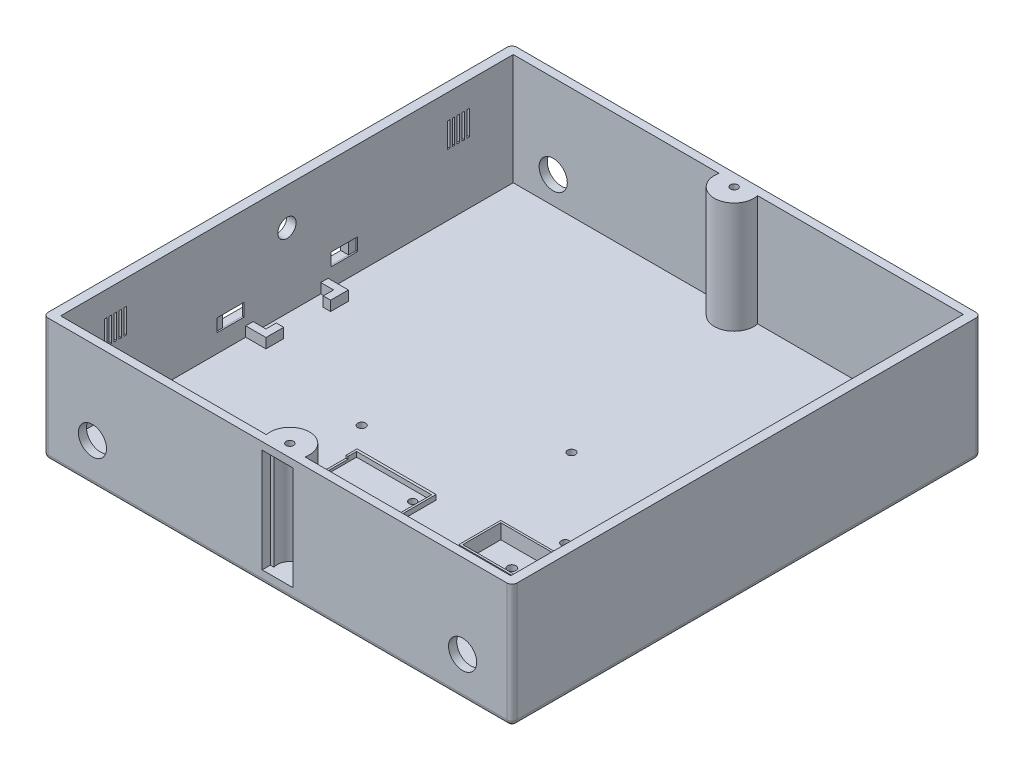
SolidWorks part; units mm, degrees
ref_plane "Front Plane" through (0, 0, 0) normal (0, 0, 1) x (1, 0, 0)
ref_plane "Top Plane" through (0, 0, 0) normal (0, 1, 0) x (1, 0, 0)
ref_plane "Right Plane" through (0, 0, 0) normal (1, 0, 0) x (0, 0, -1)
sketch "Sketch2" plane through (0, 0, 0) normal (0, 1, 0) x (1, 0, 0)
  line L0 (-97.7109, 51.5767) -> (-97.7109, -138.4233)
  line L13 (-97.7109, 51.5767) -> (92.2891, 51.5767)
  line L18 (92.2891, 51.5767) -> (92.2891, -138.4233)
  line L19 (92.2891, -138.4233) -> (-97.7109, -138.4233)
  line L20 (36.2891, -17.4233) -> (36.2891, -33.4233)
  line L21 (36.2891, -52.9016) -> (36.2891, -69.4233)
  line L52 (36.2891, -69.4233) -> (-41.7109, -69.4233)
  line L54 (-41.7109, -53.4233) -> (-41.7109, -69.4233)
  line L55 (-41.7109, -17.4233) -> (-41.7109, -33.4233)
  line L56 (36.2891, -17.4233) -> (-41.7109, -17.4233)
  line L57 (-97.7109, -43.4233) -> (92.2891, -43.4233) construction
  line L58 (-2.7109, 51.5767) -> (-2.7109, -138.4233) construction
  line L59 (-41.7109, -17.4233) -> (36.2891, -69.4233) construction
  line L60 (-41.7109, -69.4233) -> (36.2891, -17.4233)
  line L61 (-89.256, 31.0492) -> (-89.256, 49.5711)
  line L66 (46.8342, 31.0897) -> (83.8342, 31.0492)
  line L67 (46.8342, 31.0897) -> (46.8342, 49.5711)
  line L69 (46.8342, 49.5711) -> (83.8342, 49.5711)
  line L70 (83.8342, 31.0492) -> (83.8342, 49.5711)
  line L71 (83.8342, 39.0897) -> (83.8342, 41.0897)
  line L74 (46.8342, 31.0897) -> (35.8342, 31.1017)
  line L78 (46.8342, 31.0897) -> (46.8342, 49.5711)
  line L79 (46.8342, 49.5711) -> (35.8343, 49.5711)
  line L80 (35.8342, 31.1017) -> (35.8343, 49.5711)
  line L82 (21.8331, 38.6168) -> (19.8331, 38.6169)
  line L85 (21.8331, 38.6168) -> (21.8332, 43.606)
  line L90 (21.8332, 43.606) -> (19.8332, 43.606)
  line L91 (19.8331, 38.6169) -> (19.8332, 43.606)
  line L92 (21.8345, 48.6062) -> (35.8333, 48.596)
  line L93 (21.8345, 48.6062) -> (21.8342, 32.5899)
  line L94 (35.8333, 48.596) -> (35.8342, 32.5897)
  line L95 (71.8224, 30.5635) -> (75.8224, 30.5635)
  line L96 (71.8224, 30.5635) -> (71.8224, 20.5635)
  line L98 (75.8224, 30.5635) -> (75.8224, 20.5635)
  line L100 (75.8342, 49.5652) -> (75.8342, 59.5652)
  line L102 (71.8342, 49.5652) -> (75.8342, 49.5652)
  line L103 (71.8342, 49.5652) -> (71.8342, 59.5652)
  line L126 (83.8342, 39.0897) -> (88.8342, 39.0897)
  line L127 (88.8342, 39.0897) -> (88.8342, 41.0897)
  line L128 (83.8342, 41.0897) -> (88.8342, 41.0897)
  line L129 (105.7133, 53.5711) -> (40.5322, 53.5711)
  line L131 (105.7133, 53.5711) -> (105.7133, 79.0897)
  line L132 (40.5322, 53.5711) -> (40.5322, 79.0897)
  line L133 (79.8342, 53.5711) -> (67.8342, 53.5711)
  line L134 (79.8342, 53.5711) -> (79.8342, 50.7672)
  line L135 (79.8342, 50.7672) -> (67.8342, 50.7672)
  line L136 (67.8342, 53.5711) -> (67.8342, 50.7672)
  line L137 (35.8342, 32.5897) -> (21.8342, 32.5899)
  line L140 (79.8342, 50.7672) -> (79.8342, 49.5711)
  line L141 (79.8342, 49.5711) -> (67.8342, 49.5711)
  line L142 (67.8342, 49.5711) -> (67.8342, 50.7672)
  line L166 (-41.2562, 49.5711) -> (-41.256, 31.1017)
  line L167 (35.8343, 49.5711) -> (35.8342, 31.1017)
  line L169 (83.8342, 31.0492) -> (83.8342, 49.5711)
  line L171 (-73.256, 49.5711) -> (-73.256, 50.7672)
  line L172 (-85.256, 49.5711) -> (-73.256, 49.5711)
  line L173 (-85.256, 50.7672) -> (-85.256, 49.5711)
  line L175 (-41.256, 32.5897) -> (-27.256, 32.5899)
  line L176 (-73.256, 53.5711) -> (-73.256, 50.7672)
  line L178 (-85.256, 50.7672) -> (-73.256, 50.7672)
  line L179 (-85.256, 53.5711) -> (-85.256, 50.7672)
  line L181 (-85.256, 53.5711) -> (-73.256, 53.5711)
  line L182 (-45.954, 53.5711) -> (-45.954, 79.0897)
  line L185 (-111.1351, 53.5711) -> (-111.1351, 79.0897)
  line L189 (-111.1351, 53.5711) -> (-45.954, 53.5711)
  line L190 (-89.256, 41.0897) -> (-94.256, 41.0897)
  line L196 (-94.256, 39.0897) -> (-94.256, 41.0897)
  line L197 (-89.256, 39.0897) -> (-94.256, 39.0897)
  line L198 (-77.256, 49.5652) -> (-77.256, 59.5652)
  line L199 (-77.256, 49.5652) -> (-81.256, 49.5652)
  line L200 (-81.256, 49.5652) -> (-81.256, 59.5652)
  line L201 (-81.2442, 30.5635) -> (-81.2442, 20.5635)
  line L202 (-77.2442, 30.5635) -> (-77.2442, 20.5635)
  line L206 (-77.2442, 30.5635) -> (-81.2442, 30.5635)
  line L207 (-41.2551, 48.596) -> (-41.256, 32.5897)
  line L208 (-27.2563, 48.6062) -> (-27.256, 32.5899)
  line L215 (-27.2563, 48.6062) -> (-41.2551, 48.596)
  line L216 (-25.255, 38.6169) -> (-25.2551, 43.606)
  line L217 (-27.2551, 43.606) -> (-25.2551, 43.606)
  line L218 (-27.255, 38.6168) -> (-27.2551, 43.606)
  line L219 (-27.255, 38.6168) -> (-25.255, 38.6169)
  line L220 (-41.256, 31.1017) -> (-41.2562, 49.5711)
  line L221 (-52.256, 49.5711) -> (-41.2562, 49.5711)
  line L222 (-52.256, 31.0897) -> (-52.256, 49.5711)
  line L223 (-52.256, 31.0897) -> (-41.256, 31.1017)
  line L224 (-89.256, 39.0897) -> (-89.256, 41.0897)
  line L225 (-89.256, 31.0492) -> (-89.256, 49.5711)
  line L226 (-52.256, 49.5711) -> (-89.256, 49.5711)
  line L228 (-52.256, 31.0897) -> (-52.256, 49.5711)
  line L241 (-52.256, 31.0897) -> (-89.256, 31.0492)
  line L242 (40.5322, 79.0897) -> (105.7133, 79.0897)
  line L243 (71.8224, 20.5635) -> (75.8224, 20.5635)
  line L244 (-111.1351, 79.0897) -> (-45.954, 79.0897)
  line L245 (-81.256, 59.5652) -> (-77.256, 59.5652)
  line L246 (-81.2442, 20.5635) -> (-77.2442, 20.5635)
  line L247 (71.8224, -107.41) -> (75.8224, -107.41)
  line L248 (40.5322, -165.9362) -> (105.7133, -165.9362)
  line L249 (83.8342, -117.8957) -> (83.8342, -136.4176)
  line L250 (35.8343, -136.4176) -> (35.8342, -117.9482)
  line L251 (67.8342, -136.4176) -> (67.8342, -137.6137)
  line L252 (79.8342, -136.4176) -> (67.8342, -136.4176)
  line L253 (79.8342, -137.6137) -> (79.8342, -136.4176)
  line L254 (35.8342, -119.4362) -> (21.8342, -119.4364)
  line L255 (67.8342, -140.4176) -> (67.8342, -137.6137)
  line L256 (79.8342, -137.6137) -> (67.8342, -137.6137)
  line L257 (79.8342, -140.4176) -> (79.8342, -137.6137)
  line L258 (79.8342, -140.4176) -> (67.8342, -140.4176)
  line L259 (40.5322, -140.4176) -> (40.5322, -165.9362)
  line L260 (105.7133, -140.4176) -> (105.7133, -165.9362)
  line L261 (105.7133, -140.4176) -> (40.5322, -140.4176)
  line L262 (83.8342, -127.9362) -> (88.8342, -127.9362)
  line L263 (88.8342, -125.9362) -> (88.8342, -127.9362)
  line L264 (83.8342, -125.9362) -> (88.8342, -125.9362)
  line L265 (71.8342, -136.4117) -> (71.8342, -146.4117)
  line L266 (71.8342, -136.4117) -> (75.8342, -136.4117)
  line L267 (75.8342, -136.4117) -> (75.8342, -146.4117)
  line L268 (75.8224, -117.41) -> (75.8224, -107.41)
  line L269 (71.8224, -117.41) -> (71.8224, -107.41)
  line L270 (71.8224, -117.41) -> (75.8224, -117.41)
  line L271 (35.8333, -135.4425) -> (35.8342, -119.4362)
  line L272 (21.8345, -135.4527) -> (21.8342, -119.4364)
  line L273 (21.8345, -135.4527) -> (35.8333, -135.4425)
  line L274 (19.8331, -125.4634) -> (19.8332, -130.4525)
  line L275 (21.8332, -130.4525) -> (19.8332, -130.4525)
  line L276 (21.8331, -125.4634) -> (21.8332, -130.4525)
  line L277 (21.8331, -125.4634) -> (19.8331, -125.4634)
  line L278 (35.8342, -117.9482) -> (35.8343, -136.4176)
  line L279 (46.8342, -136.4176) -> (35.8343, -136.4176)
  line L280 (46.8342, -117.9362) -> (46.8342, -136.4176)
  line L281 (46.8342, -117.9362) -> (35.8342, -117.9482)
  line L282 (83.8342, -125.9362) -> (83.8342, -127.9362)
  line L283 (83.8342, -117.8957) -> (83.8342, -136.4176)
  line L284 (46.8342, -136.4176) -> (83.8342, -136.4176)
  line L285 (46.8342, -117.9362) -> (46.8342, -136.4176)
  line L286 (46.8342, -117.9362) -> (83.8342, -117.8957)
  line L287 (-81.2442, -107.41) -> (-77.2442, -107.41)
  line L288 (-81.256, -146.4117) -> (-77.256, -146.4117)
  line L289 (-111.1351, -165.9362) -> (-45.954, -165.9362)
  line L290 (-52.256, -117.9362) -> (-89.256, -117.8957)
  line L291 (-52.256, -117.9362) -> (-52.256, -136.4176)
  line L292 (-52.256, -136.4176) -> (-89.256, -136.4176)
  line L293 (-89.256, -117.8957) -> (-89.256, -136.4176)
  line L294 (-89.256, -125.9362) -> (-89.256, -127.9362)
  line L295 (-52.256, -117.9362) -> (-41.256, -117.9482)
  line L296 (-52.256, -117.9362) -> (-52.256, -136.4176)
  line L297 (-52.256, -136.4176) -> (-41.2562, -136.4176)
  line L298 (-41.256, -117.9482) -> (-41.2562, -136.4176)
  line L299 (-27.255, -125.4634) -> (-25.255, -125.4634)
  line L300 (-27.255, -125.4634) -> (-27.2551, -130.4525)
  line L301 (-27.2551, -130.4525) -> (-25.2551, -130.4525)
  line L302 (-25.255, -125.4634) -> (-25.2551, -130.4525)
  line L303 (-27.2563, -135.4527) -> (-41.2551, -135.4425)
  line L304 (-27.2563, -135.4527) -> (-27.256, -119.4364)
  line L305 (-41.2551, -135.4425) -> (-41.256, -119.4362)
  line L306 (-77.2442, -117.41) -> (-81.2442, -117.41)
  line L307 (-77.2442, -117.41) -> (-77.2442, -107.41)
  line L308 (-81.2442, -117.41) -> (-81.2442, -107.41)
  line L309 (-81.256, -136.4117) -> (-81.256, -146.4117)
  line L310 (-77.256, -136.4117) -> (-81.256, -136.4117)
  line L311 (-77.256, -136.4117) -> (-77.256, -146.4117)
  line L312 (-89.256, -125.9362) -> (-94.256, -125.9362)
  line L313 (-94.256, -125.9362) -> (-94.256, -127.9362)
  line L314 (-89.256, -127.9362) -> (-94.256, -127.9362)
  line L315 (-111.1351, -140.4176) -> (-45.954, -140.4176)
  line L316 (-111.1351, -140.4176) -> (-111.1351, -165.9362)
  line L317 (-45.954, -140.4176) -> (-45.954, -165.9362)
  line L318 (-85.256, -140.4176) -> (-73.256, -140.4176)
  line L319 (-85.256, -140.4176) -> (-85.256, -137.6137)
  line L320 (-85.256, -137.6137) -> (-73.256, -137.6137)
  line L321 (-73.256, -140.4176) -> (-73.256, -137.6137)
  line L322 (-41.256, -119.4362) -> (-27.256, -119.4364)
  line L323 (-85.256, -137.6137) -> (-85.256, -136.4176)
  line L324 (-85.256, -136.4176) -> (-73.256, -136.4176)
  line L325 (-73.256, -136.4176) -> (-73.256, -137.6137)
  line L326 (-41.2562, -136.4176) -> (-41.256, -117.9482)
  line L327 (-89.256, -117.8957) -> (-89.256, -136.4176)
  line L328 (29.0433, -79.8805) -> (64.0433, -79.883)
  line L329 (64.0433, -94.7383) -> (29.0423, -94.7383)
  line L330 (54.8427, -14.9212) -> (79.4449, -14.9212) construction
  line L331 (54.8427, -35.9212) -> (54.8427, 6.0788)
  line L332 (54.8427, -35.9212) -> (79.4449, -35.9212)
  line L333 (79.4449, -35.9212) -> (79.4449, 6.0788)
  line L334 (54.8427, 6.0788) -> (79.4449, 6.0788)
  line L335 (29.0433, -79.8805) -> (29.0423, -94.7383)
  line L336 (80.4449, -36.9212) -> (53.8427, -36.9212)
  line L337 (80.4449, -36.9212) -> (80.4449, 7.0788)
  line L338 (80.4449, 7.0788) -> (53.8427, 7.0788)
  line L339 (53.8427, -36.9212) -> (53.8427, 7.0788)
  line L340 (64.0433, -79.883) -> (64.0433, -94.7383)
  line L341 (55.0065, -87.3094) -> (55.0065, -79.8824) construction
  line L342 (55.0065, -79.8824) -> (55.0065, -94.7383) construction
  line L347 (222.9958, 221.5497) -> (222.9958, 31.5497)
  line L348 (222.9958, 31.5497) -> (412.9958, 31.5497)
  line L349 (412.9958, 31.5497) -> (412.9958, 221.5497)
  line L350 (412.9958, 221.5497) -> (222.9958, 221.5497)
  arc A8 (36.2891, -33.4233) -> (36.2891, -52.9016) centre (29.0423, -43.1624) cw
  arc A9 (-41.7109, -33.4233) -> (-41.7109, -53.4233) centre (-34.2699, -43.4233) ccw
  circle A10 centre (67.1438, -14.9212) radius 9.5
  circle A11 centre (71.0694, -87.3094) radius 9.9007
  point P21 (99.2345, 40.2078)
  point P59 (99.1669, 57.005)
  point P92 (-104.5887, 57.005)
  point P93 (-104.6563, 40.2078)
  point P130 (99.1669, -143.8515)
  point P131 (99.2345, -127.0543)
  point P168 (-104.6563, -127.0543)
  point P169 (-104.5887, -143.8515)
  point P175 (81.0405, -14.9218)
  point P188 (64.0433, -79.883)
  dimension "D1" = 1
  dimension "D2" = 1
  dimension "D3" = 190
  dimension "D4" = 190
extrude "Boss-Extrude1" add sketch "Sketch2" along normal blind 5 contours L349 L347 region at (317.9958, 0, -126.5497)
sketch "Sketch3" plane through (0, 5, 0) normal (0, 1, 0) x (1, 0, 0)
  line L0 (222.9958, 221.5497) -> (222.9958, 31.5497)
  line L1 (222.9958, 221.5497) -> (412.9958, 221.5497)
  line L2 (412.9958, 221.5497) -> (412.9958, 31.5497)
  line L3 (412.9958, 31.5497) -> (222.9958, 31.5497)
  line L4 (356.9958, 152.5497) -> (356.9958, 136.5497)
  line L5 (356.9958, 117.0714) -> (356.9958, 100.5497)
  line L6 (356.9958, 100.5497) -> (278.9958, 100.5497)
  line L7 (278.9958, 116.5497) -> (278.9958, 100.5497)
  line L8 (278.9958, 152.5497) -> (278.9958, 136.5497)
  line L9 (356.9958, 152.5497) -> (278.9958, 152.5497)
  line L10 (222.9958, 126.5497) -> (412.9958, 126.5497) construction
  line L11 (317.9958, 221.5497) -> (317.9958, 31.5497) construction
  line L12 (278.9958, 152.5497) -> (356.9958, 100.5497) construction
  line L13 (278.9958, 100.5497) -> (356.9958, 152.5497)
  line L14 (231.4507, 201.0222) -> (231.4507, 219.5441)
  line L15 (367.5408, 201.0626) -> (404.5408, 201.0222)
  line L16 (367.5408, 201.0626) -> (367.5408, 219.5441)
  line L17 (367.5408, 219.5441) -> (404.5408, 219.5441)
  line L18 (404.5408, 201.0222) -> (404.5408, 219.5441)
  line L19 (404.5408, 209.0626) -> (404.5408, 211.0626)
  line L20 (367.5408, 201.0626) -> (356.5408, 201.0747)
  line L21 (367.5408, 201.0626) -> (367.5408, 219.5441)
  line L22 (367.5408, 219.5441) -> (356.541, 219.5441)
  line L23 (356.5408, 201.0747) -> (356.541, 219.5441)
  line L24 (342.5398, 208.5898) -> (340.5398, 208.5899)
  line L25 (342.5398, 208.5898) -> (342.5399, 213.579)
  line L26 (342.5399, 213.579) -> (340.5399, 213.579)
  line L27 (340.5398, 208.5899) -> (340.5399, 213.579)
  line L28 (342.5412, 218.5792) -> (356.5399, 218.569)
  line L29 (342.5412, 218.5792) -> (342.5409, 202.5629)
  line L30 (356.5399, 218.569) -> (356.5409, 202.5626)
  line L31 (392.5291, 200.5365) -> (396.5291, 200.5365)
  line L32 (392.5291, 200.5365) -> (392.5291, 190.5365)
  line L33 (396.5291, 200.5365) -> (396.5291, 190.5365)
  line L34 (396.5408, 219.5382) -> (396.5408, 229.5382)
  line L35 (392.5408, 219.5382) -> (396.5408, 219.5382)
  line L36 (392.5408, 219.5382) -> (392.5408, 229.5382)
  line L37 (404.5408, 209.0626) -> (409.5408, 209.0626)
  line L38 (409.5408, 209.0626) -> (409.5408, 211.0626)
  line L39 (404.5408, 211.0626) -> (409.5408, 211.0626)
  line L40 (426.42, 223.5441) -> (361.2388, 223.5441)
  line L41 (426.42, 223.5441) -> (426.42, 249.0626)
  line L42 (361.2388, 223.5441) -> (361.2388, 249.0626)
  line L43 (400.5408, 223.5441) -> (388.5408, 223.5441)
  line L44 (400.5408, 223.5441) -> (400.5408, 220.7402)
  line L45 (400.5408, 220.7402) -> (388.5408, 220.7402)
  line L46 (388.5408, 223.5441) -> (388.5408, 220.7402)
  line L47 (356.5409, 202.5626) -> (342.5409, 202.5629)
  line L48 (400.5408, 220.7402) -> (400.5408, 219.5441)
  line L49 (400.5408, 219.5441) -> (388.5408, 219.5441)
  line L50 (388.5408, 219.5441) -> (388.5408, 220.7402)
  line L51 (279.4505, 219.5441) -> (279.4507, 201.0747)
  line L52 (356.541, 219.5441) -> (356.5408, 201.0747)
  line L53 (404.5408, 201.0222) -> (404.5408, 219.5441)
  line L54 (247.4507, 219.5441) -> (247.4507, 220.7402)
  line L55 (235.4507, 219.5441) -> (247.4507, 219.5441)
  line L56 (235.4507, 220.7402) -> (235.4507, 219.5441)
  line L57 (279.4507, 202.5626) -> (293.4507, 202.5629)
  line L58 (247.4507, 223.5441) -> (247.4507, 220.7402)
  line L59 (235.4507, 220.7402) -> (247.4507, 220.7402)
  line L60 (235.4507, 223.5441) -> (235.4507, 220.7402)
  line L61 (235.4507, 223.5441) -> (247.4507, 223.5441)
  line L62 (274.7527, 223.5441) -> (274.7527, 249.0626)
  line L63 (209.5716, 223.5441) -> (209.5716, 249.0626)
  line L64 (209.5716, 223.5441) -> (274.7527, 223.5441)
  line L65 (231.4507, 211.0626) -> (226.4507, 211.0626)
  line L66 (226.4507, 209.0626) -> (226.4507, 211.0626)
  line L67 (231.4507, 209.0626) -> (226.4507, 209.0626)
  line L68 (243.4507, 219.5382) -> (243.4507, 229.5382)
  line L69 (243.4507, 219.5382) -> (239.4507, 219.5382)
  line L70 (239.4507, 219.5382) -> (239.4507, 229.5382)
  line L71 (239.4624, 200.5365) -> (239.4624, 190.5365)
  line L72 (243.4624, 200.5365) -> (243.4624, 190.5365)
  line L73 (243.4624, 200.5365) -> (239.4624, 200.5365)
  line L74 (279.4516, 218.569) -> (279.4507, 202.5626)
  line L75 (293.4503, 218.5792) -> (293.4507, 202.5629)
  line L76 (293.4503, 218.5792) -> (279.4516, 218.569)
  line L77 (295.4517, 208.5899) -> (295.4516, 213.579)
  line L78 (293.4516, 213.579) -> (295.4516, 213.579)
  line L79 (293.4517, 208.5898) -> (293.4516, 213.579)
  line L80 (293.4517, 208.5898) -> (295.4517, 208.5899)
  line L81 (279.4507, 201.0747) -> (279.4505, 219.5441)
  line L82 (268.4507, 219.5441) -> (279.4505, 219.5441)
  line L83 (268.4507, 201.0626) -> (268.4507, 219.5441)
  line L84 (268.4507, 201.0626) -> (279.4507, 201.0747)
  line L85 (231.4507, 209.0626) -> (231.4507, 211.0626)
  line L86 (231.4507, 201.0222) -> (231.4507, 219.5441)
  line L87 (268.4507, 219.5441) -> (231.4507, 219.5441)
  line L88 (268.4507, 201.0626) -> (268.4507, 219.5441)
  line L89 (268.4507, 201.0626) -> (231.4507, 201.0222)
  line L90 (361.2388, 249.0626) -> (426.42, 249.0626)
  line L91 (392.5291, 190.5365) -> (396.5291, 190.5365)
  line L92 (209.5716, 249.0626) -> (274.7527, 249.0626)
  line L93 (239.4507, 229.5382) -> (243.4507, 229.5382)
  line L94 (239.4624, 190.5365) -> (243.4624, 190.5365)
  line L95 (392.5291, 62.563) -> (396.5291, 62.563)
  line L96 (361.2388, 4.0368) -> (426.42, 4.0368)
  line L97 (404.5408, 52.0772) -> (404.5408, 33.5553)
  line L98 (356.541, 33.5553) -> (356.5408, 52.0248)
  line L99 (388.5408, 33.5553) -> (388.5408, 32.3593)
  line L100 (400.5408, 33.5553) -> (388.5408, 33.5553)
  line L101 (400.5408, 32.3593) -> (400.5408, 33.5553)
  line L102 (356.5409, 50.5368) -> (342.5409, 50.5365)
  line L103 (388.5408, 29.5553) -> (388.5408, 32.3593)
  line L104 (400.5408, 32.3593) -> (388.5408, 32.3593)
  line L105 (400.5408, 29.5553) -> (400.5408, 32.3593)
  line L106 (400.5408, 29.5553) -> (388.5408, 29.5553)
  line L107 (361.2388, 29.5553) -> (361.2388, 4.0368)
  line L108 (426.42, 29.5553) -> (426.42, 4.0368)
  line L109 (426.42, 29.5553) -> (361.2388, 29.5553)
  line L110 (404.5408, 42.0368) -> (409.5408, 42.0368)
  line L111 (409.5408, 44.0368) -> (409.5408, 42.0368)
  line L112 (404.5408, 44.0368) -> (409.5408, 44.0368)
  line L113 (392.5408, 33.5613) -> (392.5408, 23.5613)
  line L114 (392.5408, 33.5613) -> (396.5408, 33.5613)
  line L115 (396.5408, 33.5613) -> (396.5408, 23.5613)
  line L116 (396.5291, 52.563) -> (396.5291, 62.563)
  line L117 (392.5291, 52.563) -> (392.5291, 62.563)
  line L118 (392.5291, 52.563) -> (396.5291, 52.563)
  line L119 (356.5399, 34.5304) -> (356.5409, 50.5368)
  line L120 (342.5412, 34.5203) -> (342.5409, 50.5365)
  line L121 (342.5412, 34.5203) -> (356.5399, 34.5304)
  line L122 (340.5398, 44.5096) -> (340.5399, 39.5205)
  line L123 (342.5399, 39.5205) -> (340.5399, 39.5205)
  line L124 (342.5398, 44.5096) -> (342.5399, 39.5205)
  line L125 (342.5398, 44.5096) -> (340.5398, 44.5096)
  line L126 (356.5408, 52.0248) -> (356.541, 33.5553)
  line L127 (367.5408, 33.5553) -> (356.541, 33.5553)
  line L128 (367.5408, 52.0368) -> (367.5408, 33.5553)
  line L129 (367.5408, 52.0368) -> (356.5408, 52.0248)
  line L130 (404.5408, 44.0368) -> (404.5408, 42.0368)
  line L131 (404.5408, 52.0772) -> (404.5408, 33.5553)
  line L132 (367.5408, 33.5553) -> (404.5408, 33.5553)
  line L133 (367.5408, 52.0368) -> (367.5408, 33.5553)
  line L134 (367.5408, 52.0368) -> (404.5408, 52.0772)
  line L135 (239.4624, 62.563) -> (243.4624, 62.563)
  line L136 (239.4507, 23.5613) -> (243.4507, 23.5613)
  line L137 (209.5716, 4.0368) -> (274.7527, 4.0368)
  line L138 (268.4507, 52.0368) -> (231.4507, 52.0772)
  line L139 (268.4507, 52.0368) -> (268.4507, 33.5553)
  line L140 (268.4507, 33.5553) -> (231.4507, 33.5553)
  line L141 (231.4507, 52.0772) -> (231.4507, 33.5553)
  line L142 (231.4507, 44.0368) -> (231.4507, 42.0368)
  line L143 (268.4507, 52.0368) -> (279.4507, 52.0248)
  line L144 (268.4507, 52.0368) -> (268.4507, 33.5553)
  line L145 (268.4507, 33.5553) -> (279.4505, 33.5553)
  line L146 (279.4507, 52.0248) -> (279.4505, 33.5553)
  line L147 (293.4517, 44.5096) -> (295.4517, 44.5096)
  line L148 (293.4517, 44.5096) -> (293.4516, 39.5205)
  line L149 (293.4516, 39.5205) -> (295.4516, 39.5205)
  line L150 (295.4517, 44.5096) -> (295.4516, 39.5205)
  line L151 (293.4503, 34.5203) -> (279.4516, 34.5304)
  line L152 (293.4503, 34.5203) -> (293.4507, 50.5365)
  line L153 (279.4516, 34.5304) -> (279.4507, 50.5368)
  line L154 (243.4624, 52.563) -> (239.4624, 52.563)
  line L155 (243.4624, 52.563) -> (243.4624, 62.563)
  line L156 (239.4624, 52.563) -> (239.4624, 62.563)
  line L157 (239.4507, 33.5613) -> (239.4507, 23.5613)
  line L158 (243.4507, 33.5613) -> (239.4507, 33.5613)
  line L159 (243.4507, 33.5613) -> (243.4507, 23.5613)
  line L160 (231.4507, 44.0368) -> (226.4507, 44.0368)
  line L161 (226.4507, 44.0368) -> (226.4507, 42.0368)
  line L162 (231.4507, 42.0368) -> (226.4507, 42.0368)
  line L163 (209.5716, 29.5553) -> (274.7527, 29.5553)
  line L164 (209.5716, 29.5553) -> (209.5716, 4.0368)
  line L165 (274.7527, 29.5553) -> (274.7527, 4.0368)
  line L166 (235.4507, 29.5553) -> (247.4507, 29.5553)
  line L167 (235.4507, 29.5553) -> (235.4507, 32.3593)
  line L168 (235.4507, 32.3593) -> (247.4507, 32.3593)
  line L169 (247.4507, 29.5553) -> (247.4507, 32.3593)
  line L170 (279.4507, 50.5368) -> (293.4507, 50.5365)
  line L171 (235.4507, 32.3593) -> (235.4507, 33.5553)
  line L172 (235.4507, 33.5553) -> (247.4507, 33.5553)
  line L173 (247.4507, 33.5553) -> (247.4507, 32.3593)
  line L174 (279.4505, 33.5553) -> (279.4507, 52.0248)
  line L175 (231.4507, 52.0772) -> (231.4507, 33.5553)
  line L192 (380.2234, 138.2947) -> (400.2234, 138.2947)
  line L194 (400.2234, 178.2947) -> (380.2234, 178.2947)
  line L195 (400.2234, 178.2947) -> (400.2234, 168.2947) construction
  line L196 (390.2234, 178.2947) -> (390.2234, 138.2947) construction
  line L197 (380.2234, 178.2947) -> (380.2234, 168.2947) construction
  line L199 (380.2234, 138.2947) -> (380.2234, 178.2947)
  line L200 (400.2234, 138.2947) -> (400.2234, 178.2947)
  line L201 (380.2234, 158.2947) -> (400.2234, 158.2947) construction
  arc A0 (356.9958, 136.5497) -> (356.9958, 117.0714) centre (349.7489, 126.8105) cw
  arc A1 (278.9958, 136.5497) -> (278.9958, 116.5497) centre (286.4367, 126.5497) ccw
  circle A5 centre (400.2234, 168.2947) radius 3
  circle A6 centre (380.2234, 168.2947) radius 3
  circle A7 centre (390.2234, 138.2947) radius 2
  circle A8 centre (390.2234, 178.2947) radius 1
  circle A9 centre (390.2234, 178.2947) radius 1.5
  circle A10 centre (400.2234, 148.2947) radius 1
  circle A11 centre (400.2234, 148.2947) radius 1.5
  circle A12 centre (380.2234, 148.2947) radius 1.5
  circle A13 centre (380.2234, 148.2947) radius 1
  circle A14 centre (390.2234, 158.2947) radius 8
  point P21 (419.9412, 210.1807)
  point P59 (419.8736, 226.978)
  point P92 (216.118, 226.978)
  point P93 (216.0503, 210.1807)
  point P130 (419.8736, 26.1215)
  point P131 (419.9412, 42.9187)
  point P168 (216.0503, 42.9187)
  point P169 (216.118, 26.1215)
  dimension "D1" = 40
  dimension "D2" = 20
sketch "Sketch4" plane through (0, 5, 0) normal (0, 1, 0) x (1, 0, 0)
  line L0 (222.9958, 221.5497) -> (222.9958, 31.5497)
  line L1 (222.9958, 221.5497) -> (412.9958, 221.5497)
  line L2 (412.9958, 221.5497) -> (412.9958, 31.5497)
  line L3 (412.9958, 31.5497) -> (222.9958, 31.5497)
  line L4 (356.9958, 152.5497) -> (356.9958, 136.5497)
  line L5 (356.9958, 117.0714) -> (356.9958, 100.5497)
  line L6 (356.9958, 100.5497) -> (278.9958, 100.5497)
  line L7 (278.9958, 116.5497) -> (278.9958, 100.5497)
  line L8 (278.9958, 152.5497) -> (278.9958, 136.5497)
  line L9 (356.9958, 152.5497) -> (278.9958, 152.5497)
  line L10 (222.9958, 126.5497) -> (412.9958, 126.5497) construction
  line L11 (317.9958, 221.5497) -> (317.9958, 31.5497) construction
  line L12 (278.9958, 152.5497) -> (356.9958, 100.5497) construction
  line L13 (278.9958, 100.5497) -> (356.9958, 152.5497)
  line L14 (231.4507, 201.0222) -> (231.4507, 219.5441)
  line L15 (367.5408, 201.0626) -> (404.5408, 201.0222)
  line L16 (367.5408, 201.0626) -> (367.5408, 219.5441)
  line L17 (367.5408, 219.5441) -> (404.5408, 219.5441)
  line L18 (404.5408, 201.0222) -> (404.5408, 219.5441)
  line L19 (404.5408, 209.0626) -> (404.5408, 211.0626)
  line L20 (367.5408, 201.0626) -> (356.5408, 201.0747)
  line L21 (367.5408, 201.0626) -> (367.5408, 219.5441)
  line L22 (367.5408, 219.5441) -> (356.541, 219.5441)
  line L23 (356.5408, 201.0747) -> (356.541, 219.5441)
  line L24 (342.5398, 208.5898) -> (340.5398, 208.5899)
  line L25 (342.5398, 208.5898) -> (342.5399, 213.579)
  line L26 (342.5399, 213.579) -> (340.5399, 213.579)
  line L27 (340.5398, 208.5899) -> (340.5399, 213.579)
  line L28 (342.5412, 218.5792) -> (356.5399, 218.569)
  line L29 (342.5412, 218.5792) -> (342.5409, 202.5629)
  line L30 (356.5399, 218.569) -> (356.5409, 202.5626)
  line L31 (392.5291, 200.5365) -> (396.5291, 200.5365)
  line L32 (392.5291, 200.5365) -> (392.5291, 190.5365)
  line L33 (396.5291, 200.5365) -> (396.5291, 190.5365)
  line L34 (396.5408, 219.5382) -> (396.5408, 229.5382)
  line L35 (392.5408, 219.5382) -> (396.5408, 219.5382)
  line L36 (392.5408, 219.5382) -> (392.5408, 229.5382)
  line L37 (404.5408, 209.0626) -> (409.5408, 209.0626)
  line L38 (409.5408, 209.0626) -> (409.5408, 211.0626)
  line L39 (404.5408, 211.0626) -> (409.5408, 211.0626)
  line L40 (426.42, 223.5441) -> (361.2388, 223.5441)
  line L41 (426.42, 223.5441) -> (426.42, 249.0626)
  line L42 (361.2388, 223.5441) -> (361.2388, 249.0626)
  line L43 (400.5408, 223.5441) -> (388.5408, 223.5441)
  line L44 (400.5408, 223.5441) -> (400.5408, 220.7402)
  line L45 (400.5408, 220.7402) -> (388.5408, 220.7402)
  line L46 (388.5408, 223.5441) -> (388.5408, 220.7402)
  line L47 (356.5409, 202.5626) -> (342.5409, 202.5629)
  line L48 (400.5408, 220.7402) -> (400.5408, 219.5441)
  line L49 (400.5408, 219.5441) -> (388.5408, 219.5441)
  line L50 (388.5408, 219.5441) -> (388.5408, 220.7402)
  line L51 (279.4505, 219.5441) -> (279.4507, 201.0747)
  line L52 (356.541, 219.5441) -> (356.5408, 201.0747)
  line L53 (404.5408, 201.0222) -> (404.5408, 219.5441)
  line L54 (247.4507, 219.5441) -> (247.4507, 220.7402)
  line L55 (235.4507, 219.5441) -> (247.4507, 219.5441)
  line L56 (235.4507, 220.7402) -> (235.4507, 219.5441)
  line L57 (279.4507, 202.5626) -> (293.4507, 202.5629)
  line L58 (247.4507, 223.5441) -> (247.4507, 220.7402)
  line L59 (235.4507, 220.7402) -> (247.4507, 220.7402)
  line L60 (235.4507, 223.5441) -> (235.4507, 220.7402)
  line L61 (235.4507, 223.5441) -> (247.4507, 223.5441)
  line L62 (274.7527, 223.5441) -> (274.7527, 249.0626)
  line L63 (209.5716, 223.5441) -> (209.5716, 249.0626)
  line L64 (209.5716, 223.5441) -> (274.7527, 223.5441)
  line L65 (231.4507, 211.0626) -> (226.4507, 211.0626)
  line L66 (226.4507, 209.0626) -> (226.4507, 211.0626)
  line L67 (231.4507, 209.0626) -> (226.4507, 209.0626)
  line L68 (243.4507, 219.5382) -> (243.4507, 229.5382)
  line L69 (243.4507, 219.5382) -> (239.4507, 219.5382)
  line L70 (239.4507, 219.5382) -> (239.4507, 229.5382)
  line L71 (239.4624, 200.5365) -> (239.4624, 190.5365)
  line L72 (243.4624, 200.5365) -> (243.4624, 190.5365)
  line L73 (243.4624, 200.5365) -> (239.4624, 200.5365)
  line L74 (279.4516, 218.569) -> (279.4507, 202.5626)
  line L75 (293.4503, 218.5792) -> (293.4507, 202.5629)
  line L76 (293.4503, 218.5792) -> (279.4516, 218.569)
  line L77 (295.4517, 208.5899) -> (295.4516, 213.579)
  line L78 (293.4516, 213.579) -> (295.4516, 213.579)
  line L79 (293.4517, 208.5898) -> (293.4516, 213.579)
  line L80 (293.4517, 208.5898) -> (295.4517, 208.5899)
  line L81 (279.4507, 201.0747) -> (279.4505, 219.5441)
  line L82 (268.4507, 219.5441) -> (279.4505, 219.5441)
  line L83 (268.4507, 201.0626) -> (268.4507, 219.5441)
  line L84 (268.4507, 201.0626) -> (279.4507, 201.0747)
  line L85 (231.4507, 209.0626) -> (231.4507, 211.0626)
  line L86 (231.4507, 201.0222) -> (231.4507, 219.5441)
  line L87 (268.4507, 219.5441) -> (231.4507, 219.5441)
  line L88 (268.4507, 201.0626) -> (268.4507, 219.5441)
  line L89 (268.4507, 201.0626) -> (231.4507, 201.0222)
  line L90 (361.2388, 249.0626) -> (426.42, 249.0626)
  line L91 (392.5291, 190.5365) -> (396.5291, 190.5365)
  line L92 (209.5716, 249.0626) -> (274.7527, 249.0626)
  line L93 (239.4507, 229.5382) -> (243.4507, 229.5382)
  line L94 (239.4624, 190.5365) -> (243.4624, 190.5365)
  line L95 (392.5291, 62.563) -> (396.5291, 62.563)
  line L96 (361.2388, 4.0368) -> (426.42, 4.0368)
  line L97 (404.5408, 52.0772) -> (404.5408, 33.5553)
  line L98 (356.541, 33.5553) -> (356.5408, 52.0248)
  line L99 (388.5408, 33.5553) -> (388.5408, 32.3593)
  line L100 (400.5408, 33.5553) -> (388.5408, 33.5553)
  line L101 (400.5408, 32.3593) -> (400.5408, 33.5553)
  line L102 (356.5409, 50.5368) -> (342.5409, 50.5365)
  line L103 (388.5408, 29.5553) -> (388.5408, 32.3593)
  line L104 (400.5408, 32.3593) -> (388.5408, 32.3593)
  line L105 (400.5408, 29.5553) -> (400.5408, 32.3593)
  line L106 (400.5408, 29.5553) -> (388.5408, 29.5553)
  line L107 (361.2388, 29.5553) -> (361.2388, 4.0368)
  line L108 (426.42, 29.5553) -> (426.42, 4.0368)
  line L109 (426.42, 29.5553) -> (361.2388, 29.5553)
  line L110 (404.5408, 42.0368) -> (409.5408, 42.0368)
  line L111 (409.5408, 44.0368) -> (409.5408, 42.0368)
  line L112 (404.5408, 44.0368) -> (409.5408, 44.0368)
  line L113 (392.5408, 33.5613) -> (392.5408, 23.5613)
  line L114 (392.5408, 33.5613) -> (396.5408, 33.5613)
  line L115 (396.5408, 33.5613) -> (396.5408, 23.5613)
  line L116 (396.5291, 52.563) -> (396.5291, 62.563)
  line L117 (392.5291, 52.563) -> (392.5291, 62.563)
  line L118 (392.5291, 52.563) -> (396.5291, 52.563)
  line L119 (356.5399, 34.5304) -> (356.5409, 50.5368)
  line L120 (342.5412, 34.5203) -> (342.5409, 50.5365)
  line L121 (342.5412, 34.5203) -> (356.5399, 34.5304)
  line L122 (340.5398, 44.5096) -> (340.5399, 39.5205)
  line L123 (342.5399, 39.5205) -> (340.5399, 39.5205)
  line L124 (342.5398, 44.5096) -> (342.5399, 39.5205)
  line L125 (342.5398, 44.5096) -> (340.5398, 44.5096)
  line L126 (356.5408, 52.0248) -> (356.541, 33.5553)
  line L127 (367.5408, 33.5553) -> (356.541, 33.5553)
  line L128 (367.5408, 52.0368) -> (367.5408, 33.5553)
  line L129 (367.5408, 52.0368) -> (356.5408, 52.0248)
  line L130 (404.5408, 44.0368) -> (404.5408, 42.0368)
  line L131 (404.5408, 52.0772) -> (404.5408, 33.5553)
  line L132 (367.5408, 33.5553) -> (404.5408, 33.5553)
  line L133 (367.5408, 52.0368) -> (367.5408, 33.5553)
  line L134 (367.5408, 52.0368) -> (404.5408, 52.0772)
  line L135 (239.4624, 62.563) -> (243.4624, 62.563)
  line L136 (239.4507, 23.5613) -> (243.4507, 23.5613)
  line L137 (209.5716, 4.0368) -> (274.7527, 4.0368)
  line L138 (268.4507, 52.0368) -> (231.4507, 52.0772)
  line L139 (268.4507, 52.0368) -> (268.4507, 33.5553)
  line L140 (268.4507, 33.5553) -> (231.4507, 33.5553)
  line L141 (231.4507, 52.0772) -> (231.4507, 33.5553)
  line L142 (231.4507, 44.0368) -> (231.4507, 42.0368)
  line L143 (268.4507, 52.0368) -> (279.4507, 52.0248)
  line L144 (268.4507, 52.0368) -> (268.4507, 33.5553)
  line L145 (268.4507, 33.5553) -> (279.4505, 33.5553)
  line L146 (279.4507, 52.0248) -> (279.4505, 33.5553)
  line L147 (293.4517, 44.5096) -> (295.4517, 44.5096)
  line L148 (293.4517, 44.5096) -> (293.4516, 39.5205)
  line L149 (293.4516, 39.5205) -> (295.4516, 39.5205)
  line L150 (295.4517, 44.5096) -> (295.4516, 39.5205)
  line L151 (293.4503, 34.5203) -> (279.4516, 34.5304)
  line L152 (293.4503, 34.5203) -> (293.4507, 50.5365)
  line L153 (279.4516, 34.5304) -> (279.4507, 50.5368)
  line L154 (243.4624, 52.563) -> (239.4624, 52.563)
  line L155 (243.4624, 52.563) -> (243.4624, 62.563)
  line L156 (239.4624, 52.563) -> (239.4624, 62.563)
  line L157 (239.4507, 33.5613) -> (239.4507, 23.5613)
  line L158 (243.4507, 33.5613) -> (239.4507, 33.5613)
  line L159 (243.4507, 33.5613) -> (243.4507, 23.5613)
  line L160 (231.4507, 44.0368) -> (226.4507, 44.0368)
  line L161 (226.4507, 44.0368) -> (226.4507, 42.0368)
  line L162 (231.4507, 42.0368) -> (226.4507, 42.0368)
  line L163 (209.5716, 29.5553) -> (274.7527, 29.5553)
  line L164 (209.5716, 29.5553) -> (209.5716, 4.0368)
  line L165 (274.7527, 29.5553) -> (274.7527, 4.0368)
  line L166 (235.4507, 29.5553) -> (247.4507, 29.5553)
  line L167 (235.4507, 29.5553) -> (235.4507, 32.3593)
  line L168 (235.4507, 32.3593) -> (247.4507, 32.3593)
  line L169 (247.4507, 29.5553) -> (247.4507, 32.3593)
  line L170 (279.4507, 50.5368) -> (293.4507, 50.5365)
  line L171 (235.4507, 32.3593) -> (235.4507, 33.5553)
  line L172 (235.4507, 33.5553) -> (247.4507, 33.5553)
  line L173 (247.4507, 33.5553) -> (247.4507, 32.3593)
  line L174 (279.4505, 33.5553) -> (279.4507, 52.0248)
  line L175 (231.4507, 52.0772) -> (231.4507, 33.5553)
  line L176 (349.75, 90.0925) -> (384.75, 90.09)
  line L177 (384.75, 75.2347) -> (349.7489, 75.2347)
  line L178 (349.75, 90.0925) -> (349.7489, 75.2347)
  line L179 (384.75, 90.09) -> (384.75, 75.2347)
  line L180 (375.7131, 82.6636) -> (375.7131, 90.0906) construction
  line L181 (375.7131, 90.0906) -> (375.7131, 75.2347) construction
  line L182 (380.2234, 138.2947) -> (400.2234, 138.2947)
  line L183 (400.2234, 178.2947) -> (380.2234, 178.2947)
  line L184 (400.2234, 178.2947) -> (400.2234, 168.2947) construction
  line L185 (390.2234, 178.2947) -> (390.2234, 138.2947) construction
  line L186 (380.2234, 178.2947) -> (380.2234, 168.2947) construction
  line L187 (380.2234, 138.2947) -> (380.2234, 178.2947)
  line L188 (400.2234, 138.2947) -> (400.2234, 178.2947)
  line L189 (380.2234, 158.2947) -> (400.2234, 158.2947) construction
  line L190 (380.2234, 178.2947) -> (380.2234, 138.2947) construction
  line L191 (380.2234, 138.2947) -> (400.2234, 138.2947) construction
  line L192 (400.2234, 138.2947) -> (400.2234, 178.2947) construction
  line L193 (400.2234, 178.2947) -> (380.2234, 178.2947) construction
  line L194 (400.2234, 178.2947) -> (394.2234, 178.2947)
  line L195 (394.2234, 178.2947) -> (394.2234, 172.2947)
  line L196 (394.2234, 172.2947) -> (400.2234, 172.2947)
  line L197 (400.2234, 172.2947) -> (400.2234, 178.2947)
  line L198 (380.2234, 158.2947) -> (400.2234, 158.2947) construction
  line L199 (390.2234, 178.2947) -> (390.2234, 138.2947) construction
  line L200 (380.2234, 172.2947) -> (380.2234, 178.2947)
  line L201 (386.2234, 172.2947) -> (380.2234, 172.2947)
  line L202 (386.2234, 178.2947) -> (386.2234, 172.2947)
  line L203 (380.2234, 178.2947) -> (386.2234, 178.2947)
  line L204 (400.2234, 144.2947) -> (400.2234, 138.2947)
  line L205 (394.2234, 144.2947) -> (400.2234, 144.2947)
  line L206 (394.2234, 138.2947) -> (394.2234, 144.2947)
  line L207 (400.2234, 138.2947) -> (394.2234, 138.2947)
  line L208 (380.2234, 138.2947) -> (386.2234, 138.2947)
  line L209 (386.2234, 138.2947) -> (386.2234, 144.2947)
  line L210 (386.2234, 144.2947) -> (380.2234, 144.2947)
  line L211 (380.2234, 144.2947) -> (380.2234, 138.2947)
  arc A0 (356.9958, 136.5497) -> (356.9958, 117.0714) centre (349.7489, 126.8105) cw
  arc A1 (278.9958, 136.5497) -> (278.9958, 116.5497) centre (286.4367, 126.5497) ccw
  circle A2 centre (391.776, 82.6636) radius 9.9007
  circle A3 centre (400.2234, 168.2947) radius 3
  circle A4 centre (380.2234, 168.2947) radius 3
  circle A5 centre (390.2234, 138.2947) radius 2
  circle A6 centre (390.2234, 178.2947) radius 1
  circle A7 centre (390.2234, 178.2947) radius 1.5
  circle A8 centre (400.2234, 148.2947) radius 1
  circle A9 centre (400.2234, 148.2947) radius 1.5
  circle A10 centre (380.2234, 148.2947) radius 1.5
  circle A11 centre (380.2234, 148.2947) radius 1
  circle A12 centre (390.2234, 158.2947) radius 8
  point P21 (419.9412, 210.1807)
  point P59 (419.8736, 226.978)
  point P92 (216.118, 226.978)
  point P93 (216.0503, 210.1807)
  point P130 (419.8736, 26.1215)
  point P131 (419.9412, 42.9187)
  point P168 (216.0503, 42.9187)
  point P169 (216.118, 26.1215)
  point P175 (384.75, 90.09)
  dimension "D3" = 20
extrude "Boss-Extrude2" add sketch "Sketch4" along normal blind 3 contours L195 L196 L188 L183 | L202 L183 L187 L201 | L209 L210 L187 L182 | L206 L182 L188 L205 region at (383.2234, 5, -141.2947) region at (397.2234, 5, -141.2947) region at (383.2234, 5, -175.2947) region at (397.2234, 5, -175.2947)
sketch "Sketch5" plane through (0, 5, 0) normal (0, 1, 0) x (1, 0, 0)
sketch "Sketch7" plane through (0, 5, 0) normal (0, 1, 0) x (1, 0, 0)
  line L0 (380.2234, 138.2947) -> (400.2234, 138.2947)
  line L1 (400.2234, 178.2947) -> (380.2234, 178.2947)
  line L2 (400.2234, 178.2947) -> (400.2234, 168.2947) construction
  line L3 (390.2234, 178.2947) -> (390.2234, 138.2947) construction
  line L4 (380.2234, 178.2947) -> (380.2234, 168.2947) construction
  line L5 (380.2234, 138.2947) -> (380.2234, 178.2947)
  line L6 (400.2234, 138.2947) -> (400.2234, 178.2947)
  line L7 (380.2234, 158.2947) -> (400.2234, 158.2947) construction
  line L8 (380.2234, 178.2947) -> (380.2234, 138.2947) construction
  line L9 (380.2234, 138.2947) -> (400.2234, 138.2947) construction
  line L10 (400.2234, 138.2947) -> (400.2234, 178.2947) construction
  line L11 (400.2234, 178.2947) -> (380.2234, 178.2947) construction
  line L12 (400.2234, 178.2947) -> (394.2234, 178.2947)
  line L13 (394.2234, 178.2947) -> (394.2234, 172.2947)
  line L14 (394.2234, 172.2947) -> (400.2234, 172.2947)
  line L15 (400.2234, 172.2947) -> (400.2234, 178.2947)
  line L16 (380.2234, 158.2947) -> (400.2234, 158.2947) construction
  line L17 (390.2234, 178.2947) -> (390.2234, 138.2947) construction
  line L18 (380.2234, 172.2947) -> (380.2234, 178.2947)
  line L19 (386.2234, 172.2947) -> (380.2234, 172.2947)
  line L20 (386.2234, 178.2947) -> (386.2234, 172.2947)
  line L21 (380.2234, 178.2947) -> (386.2234, 178.2947)
  line L22 (400.2234, 144.2947) -> (400.2234, 138.2947)
  line L23 (394.2234, 144.2947) -> (400.2234, 144.2947)
  line L24 (394.2234, 138.2947) -> (394.2234, 144.2947)
  line L25 (400.2234, 138.2947) -> (394.2234, 138.2947)
  line L26 (380.2234, 138.2947) -> (386.2234, 138.2947)
  line L27 (386.2234, 138.2947) -> (386.2234, 144.2947)
  line L28 (386.2234, 144.2947) -> (380.2234, 144.2947)
  line L29 (380.2234, 144.2947) -> (380.2234, 138.2947)
  line L30 (380.2234, 178.2947) -> (380.2234, 178.4947)
  line L31 (380.2234, 178.4947) -> (388.7234, 178.4947)
  line L32 (400.2234, 178.2947) -> (400.2234, 178.4947)
  line L33 (400.2234, 178.4947) -> (391.9116, 178.4947)
  line L34 (400.2234, 178.2947) -> (400.4234, 178.2947)
  line L35 (400.2234, 178.4947) -> (400.4234, 178.4947)
  line L36 (400.4234, 178.4947) -> (400.4234, 171.288)
  line L37 (380.2234, 178.2947) -> (380.0234, 178.2947)
  line L38 (380.2234, 178.4947) -> (380.0234, 178.4947)
  line L39 (380.0234, 178.4947) -> (380.0234, 171.288)
  line L40 (400.2234, 138.2947) -> (400.4234, 138.2947)
  line L41 (400.4234, 138.2947) -> (400.4234, 146.8081)
  line L42 (400.4234, 149.7813) -> (400.4234, 165.3014)
  line L43 (400.2234, 138.2947) -> (400.2234, 138.0947)
  line L44 (400.4234, 138.2947) -> (400.4234, 138.0947)
  line L45 (400.4234, 138.0947) -> (392.2134, 138.0947)
  line L46 (380.2234, 178.4947) -> (388.5352, 178.4947)
  line L47 (380.0234, 178.4947) -> (380.0234, 171.288)
  line L48 (380.0234, 149.7813) -> (380.0234, 165.3014)
  line L49 (380.0234, 138.2947) -> (380.0234, 146.8081)
  line L50 (380.0234, 138.2947) -> (380.0234, 138.0947)
  line L51 (380.0234, 138.0947) -> (388.2334, 138.0947)
  line L52 (400.4234, 178.2947) -> (401.2234, 178.2947)
  line L53 (401.2234, 178.2947) -> (401.2234, 171.1231)
  line L54 (400.4234, 178.4947) -> (400.4234, 179.2947)
  line L55 (401.2234, 179.2947) -> (392.5147, 179.2947)
  line L56 (401.2234, 179.2947) -> (401.2234, 178.2947)
  line L57 (400.2234, 138.0947) -> (400.2234, 137.2947)
  line L58 (400.4234, 138.2947) -> (401.2234, 138.2947)
  line L59 (400.2234, 137.2947) -> (380.0234, 137.2947)
  line L60 (380.0234, 137.4243) -> (380.0234, 138.0947)
  line L61 (380.0234, 137.2947) -> (380.0234, 137.4243)
  line L62 (388.2334, 138.0947) -> (392.2134, 138.0947)
  line L63 (401.2234, 138.2947) -> (401.2234, 146.0034)
  line L64 (401.2234, 150.586) -> (401.2234, 165.4663)
  line L65 (400.2234, 137.2947) -> (401.2234, 137.2947)
  line L66 (401.2234, 137.2947) -> (401.2234, 138.2947)
  line L67 (379.2234, 179.2947) -> (387.9321, 179.2947)
  line L68 (379.2234, 179.2947) -> (379.2234, 178.2947)
  line L69 (379.2234, 178.2947) -> (379.2234, 171.1231)
  line L70 (379.2234, 150.586) -> (379.2234, 165.4663)
  line L71 (379.2234, 138.2947) -> (379.2234, 146.0034)
  line L72 (379.2234, 137.2947) -> (379.2234, 138.2947)
  line L73 (380.2234, 137.2947) -> (379.2234, 137.2947)
  line L74 (380.2234, 137.2947) -> (400.4234, 137.2947)
  line L75 (400.4234, 165.3014) -> (400.4234, 165.5018)
  line L76 (400.4234, 171.288) -> (400.4234, 171.0875)
  line L77 (401.2234, 171.1231) -> (401.2234, 170.91)
  line L78 (400.2234, 171.0947) -> (400.2234, 165.4947)
  line L79 (380.0234, 165.3014) -> (380.0234, 165.5018)
  line L80 (379.2234, 165.4663) -> (379.2234, 166.3773)
  line L81 (380.0234, 171.288) -> (380.0234, 171.0875)
  line L82 (379.2234, 171.1231) -> (379.2234, 170.91)
  line L83 (401.2234, 166.3773) -> (400.4234, 166.3773)
  line L84 (400.4234, 166.3773) -> (400.4234, 165.5018)
  line L85 (401.2234, 170.91) -> (401.2234, 170.7492)
  line L86 (401.2234, 170.7492) -> (400.4234, 170.7492)
  line L87 (400.4234, 170.7492) -> (400.4234, 171.0875)
  line L88 (379.2234, 170.91) -> (379.2234, 170.7492)
  line L89 (379.2234, 170.7492) -> (380.0234, 170.7492)
  line L90 (380.0234, 170.7492) -> (380.0234, 171.0468)
  line L91 (379.2234, 166.3773) -> (380.0234, 166.3773)
  line L92 (380.0234, 166.3773) -> (380.0234, 165.5018)
  circle A0 centre (400.2234, 168.2947) radius 3
  circle A1 centre (380.2234, 168.2947) radius 3
  circle A2 centre (390.2234, 138.2947) radius 2
  circle A3 centre (390.2234, 178.2947) radius 1
  circle A4 centre (390.2234, 178.2947) radius 1.5
  circle A5 centre (400.2234, 148.2947) radius 1
  circle A6 centre (400.2234, 148.2947) radius 1.5
  circle A7 centre (380.2234, 148.2947) radius 1.5
  circle A8 centre (380.2234, 148.2947) radius 1
  circle A9 centre (390.2234, 158.2947) radius 8
  circle A10 centre (390.2234, 178.2947) radius 1.7
  circle A11 centre (400.2234, 168.2947) radius 2.8
  circle A12 centre (380.2234, 168.2947) radius 2.8
  circle A13 centre (400.2234, 148.2947) radius 1.7
  circle A14 centre (380.2234, 148.2947) radius 1.7
  circle A15 centre (390.2234, 178.2947) radius 2.5
  circle A16 centre (400.2234, 148.2947) radius 2.5
  circle A17 centre (380.2234, 148.2947) radius 2.5
  circle A18 centre (400.2234, 168.2947) radius 2.8
  point P87 (401.2234, 137.7947)
  point P97 (379.2234, 137.7947)
  dimension "D5" = 0.2
  dimension "D1" = 40
  dimension "D2" = 20
  dimension "D3" = 20
  dimension "D4" = 40
extrude "Boss-Extrude5" add sketch "Sketch7" along normal blind 6 contours A16 L64 A0 L42 | A16 L41 L58 L63 | L65 L66 L58 L44 L45 L57 | A2 L59 L57 L45 | A0 L53 L52 L36 | L56 L55 L54 L36 L52 | A15 L33 L35 L54 L55 | A15 L67 L68 L69 A1 L39 L38 L31 | L70 A17 L48 A1 | L49 A17 L71 L72 L73 L61 L60 L50 | A2 L51 L60 L61 L59 | L74 A2 L62 | L41 A16 L42 A13 | A17 L49 A14 L48 | L33 A15 L46 A10 | A11 | A12 region at (384.1776, 5, -137.6926) region at (390.2234, 5, -137.7037) region at (379.6284, 5, -145.9231) region at (379.6219, 5, -141.5873) region at (396.1693, 5, -137.6926) region at (400.7401, 5, -137.778) region at (379.6218, 5, -158.0373) region at (400.8252, 5, -142.0873) region at (400.4783, 5, -146.2046) region at (379.3428, 5, -174.7089) region at (400.8251, 5, -158.0373) region at (390.2234, 5, -180.7398) region at (400.825, 5, -174.7595) region at (396.5308, 5, -178.8964) region at (400.8234, 5, -178.7947)
sketch "Sketch20" plane through (0, 5, 0) normal (0, 1, 0) x (1, 0, 0)
  line L4 (376.9958, 54.0497) -> (376.9958, 35.0497)
  line L5 (376.9958, 35.0497) -> (408.9958, 35.0497)
  line L6 (408.9958, 35.0497) -> (408.9958, 54.0497)
  line L7 (408.9958, 54.0497) -> (376.9958, 54.0497)
  line L8 (412.9958, 221.5497) -> (412.9958, 31.5497) construction
  line L9 (412.9958, 31.5497) -> (222.9958, 31.5497) construction
  line L10 (222.9958, 126.5497) -> (412.9958, 126.5497) construction
  line L11 (408.9958, 199.0497) -> (376.9958, 199.0497)
  line L12 (408.9958, 218.0497) -> (408.9958, 199.0497)
  line L13 (376.9958, 218.0497) -> (408.9958, 218.0497)
  line L14 (376.9958, 199.0497) -> (376.9958, 218.0497)
  line L15 (317.9958, 221.5497) -> (317.9958, 31.5497) construction
  line L16 (258.9958, 199.0497) -> (258.9958, 218.0497)
  line L17 (258.9958, 218.0497) -> (226.9958, 218.0497)
  line L18 (226.9958, 218.0497) -> (226.9958, 199.0497)
  line L19 (226.9958, 199.0497) -> (258.9958, 199.0497)
  line L20 (226.9958, 54.0497) -> (258.9958, 54.0497)
  line L21 (226.9958, 35.0497) -> (226.9958, 54.0497)
  line L22 (258.9958, 35.0497) -> (226.9958, 35.0497)
  line L23 (258.9958, 54.0497) -> (258.9958, 35.0497)
  line L24 (408.9958, 35.0497) -> (408.9958, 34.8497) construction
  line L25 (408.9958, 35.0497) -> (409.1958, 35.0497) construction
  line L26 (408.9958, 218.0497) -> (408.9958, 218.2497) construction
  line L27 (408.9958, 218.0497) -> (409.1895, 218.0497) construction
  line L28 (226.9958, 35.0497) -> (226.7958, 35.0497) construction
  line L29 (226.9958, 35.0497) -> (226.9958, 34.8497) construction
  line L30 (226.9958, 218.0497) -> (226.802, 218.0497) construction
  line L31 (226.9958, 218.0497) -> (226.9958, 218.2497) construction
  line L37 (412.9958, 31.5497) -> (222.9958, 31.5497)
  line L39 (222.9958, 221.5497) -> (412.9958, 221.5497)
  line L40 (412.9958, 126.5497) -> (402.9958, 126.5497)
  line L41 (412.9958, 221.5497) -> (412.9958, 132.7947)
  line L42 (412.9958, 31.5497) -> (412.9958, 221.5497) construction
  line L43 (222.9958, 120.3047) -> (222.9958, 31.5497)
  line L44 (409.1958, 34.8497) -> (409.1958, 118.6402)
  line L45 (409.1895, 218.2497) -> (409.1895, 134.4602)
  line L48 (409.1895, 218.2497) -> (226.7958, 218.2497)
  line L49 (412.9958, 120.3047) -> (412.9958, 31.5497)
  line L50 (412.9958, 31.5497) -> (222.9958, 31.5497)
  line L51 (222.9958, 221.5497) -> (222.9958, 132.7947)
  line L52 (222.9958, 221.5497) -> (412.9958, 221.5497)
  line L53 (226.7958, 218.2497) -> (226.7958, 134.4592)
  line L55 (222.9958, 221.5497) -> (222.9958, 31.5497) construction
  line L56 (226.7958, 134.4592) -> (226.7958, 118.6402)
  line L58 (226.7958, 34.8497) -> (226.7958, 118.6402)
  line L59 (226.7958, 34.8497) -> (409.1958, 34.8497)
  circle A5 centre (407.9958, 126.5497) radius 8
  circle A6 centre (407.9958, 126.5497) radius 3
  circle A10 centre (407.9958, 126.5497) radius 5
  point P68 (409.1895, 134.4602)
  point P69 (409.1895, 134.4602)
  point P70 (409.1895, 134.4602)
  point P71 (409.1895, 134.4602)
  line M57 (412.9958, 31.5497) -> (412.9958, 221.5497)
  line M58 (412.9958, 221.5497) -> (222.9958, 221.5497)
  line M59 (222.9958, 221.5497) -> (222.9958, 31.5497)
  line M60 (222.9958, 31.5497) -> (412.9958, 31.5497)
  dimension "D1" = 32
  dimension "D2" = 19
  dimension "D3" = 4
  dimension "D4" = 3.5
extrude "Boss-Extrude10" add sketch "Sketch20" along normal blind 45 contours M60 M57 M58 M59 region at (317.9958, 5, -34.2367)
sketch "Sketch9" plane through (0, 5, 0) normal (0, 1, 0) x (1, 0, 0)
sketch "Sketch10" plane through (0, 5, 0) normal (0, 1, 0) x (1, 0, 0)
  line L0 (400.4234, 171.288) -> (400.4234, 165.3014)
  line L1 (400.4234, 165.3014) -> (401.2234, 165.3014)
  line L2 (401.2234, 150.586) -> (401.2234, 165.4663) construction
  line L3 (401.2234, 165.3014) -> (401.2234, 171.3379)
  line L4 (401.2234, 179.2947) -> (401.2234, 171.1231) construction
  line L5 (401.2234, 171.3379) -> (400.4234, 171.3379)
  line L7 (400.4234, 178.4947) -> (400.4234, 171.288) construction
  line L8 (400.4234, 171.3379) -> (400.4234, 171.288)
extrude "Boss-Extrude6" add sketch "Sketch10" along normal blind 6
sketch "Sketch11" plane through (0, 5, 0) normal (0, 1, 0) x (1, 0, 0)
  line L0 (379.2234, 171.1231) -> (379.2234, 165.0919)
  line L1 (379.2234, 150.586) -> (379.2234, 165.4663) construction
  line L2 (379.2234, 165.0919) -> (380.0234, 165.0919)
  line L3 (380.0234, 149.9829) -> (380.0234, 165.3014) construction
  line L4 (380.0234, 165.0919) -> (380.0234, 171.6036)
  line L5 (380.0234, 178.4947) -> (380.0234, 171.288) construction
  line L6 (380.0234, 171.6036) -> (379.2234, 171.6036)
  line L7 (379.2234, 179.2947) -> (379.2234, 171.1231) construction
  line L8 (379.2234, 171.6036) -> (379.2234, 171.1231)
extrude "Boss-Extrude7" add sketch "Sketch11" along normal blind 6
sketch "Sketch12" plane through (0, 5, 0) normal (0, 1, 0) x (1, 0, 0)
  line L0 (401.2234, 171.3183) -> (401.2234, 165.1255)
  line L1 (401.2234, 179.2947) -> (401.2234, 170.91) construction
  line L2 (401.2234, 150.586) -> (401.2234, 165.6794) construction
  line L3 (401.2234, 170.91) -> (401.2234, 165.6794)
  arc A1 (400.2234, 171.0947) -> (400.2234, 165.4947) centre (400.2234, 168.2947) cw
sketch "Sketch13" plane through (0, 5, 0) normal (0, 1, 0) x (1, 0, 0)
  line L0 (379.2234, 171.3493) -> (379.2234, 165.133)
  line L1 (379.2234, 179.2947) -> (379.2234, 170.91) construction
  line L2 (379.2234, 150.586) -> (379.2234, 165.6794) construction
  line L3 (379.2234, 165.133) -> (380.0234, 165.133)
  line L4 (380.0234, 149.9829) -> (380.0234, 165.5018) construction
  line L5 (380.0234, 165.133) -> (380.0234, 171.3493)
  line L6 (380.0234, 178.4947) -> (380.0234, 171.0875) construction
  line L7 (380.0234, 171.3493) -> (379.2234, 171.3493)
  circle A0 centre (380.2234, 168.2947) radius 2.8
extrude "Cut-Extrude6" cut sketch "Sketch13" along normal blind 6 contours L0 A0 region at (378.479, 5, -168.2947)
sketch "Sketch14" plane through (0, 5, 0) normal (0, 1, 0) x (1, 0, 0)
  line L0 (349.7489, 75.2347) -> (387.7489, 75.2347)
  line L2 (387.7489, 75.2347) -> (387.7489, 90.2347)
  line L4 (387.7489, 90.2347) -> (349.7489, 90.2347)
  line L5 (349.7489, 90.2347) -> (349.7489, 75.2347)
  line L6 (349.7489, 82.7347) -> (389.7489, 82.7347) construction
  line L7 (349.7489, 75.2347) -> (349.5489, 75.2347)
  line L8 (349.7489, 90.2347) -> (349.5489, 90.2347)
  line L9 (349.7489, 90.2347) -> (349.7489, 90.4419)
  line L10 (349.7489, 75.2347) -> (349.7489, 75.0419)
  line L11 (387.7489, 75.2347) -> (387.7489, 75.0419)
  line L12 (387.7489, 90.2347) -> (387.7489, 90.4419)
  line L13 (387.7489, 90.2347) -> (387.9489, 90.2347)
  line L14 (387.7489, 75.2347) -> (387.9489, 75.2347)
  line L15 (349.5489, 75.0419) -> (349.5489, 90.4419)
  line L16 (349.5489, 90.4419) -> (387.9489, 90.4419)
  line L17 (387.9489, 90.4419) -> (387.9489, 75.0419)
  line L18 (387.9489, 75.0419) -> (349.5489, 75.0419)
  line L19 (387.9489, 75.0419) -> (387.9489, 74.2419)
  line L20 (387.9489, 75.0419) -> (388.7489, 75.0419)
  line L21 (387.9489, 90.4419) -> (388.7489, 90.4419)
  line L22 (387.9489, 90.4419) -> (387.9489, 91.2419)
  line L23 (349.5489, 90.4419) -> (349.5489, 91.2419)
  line L24 (349.5106, 90.4419) -> (348.7106, 90.4419)
  line L25 (349.5489, 75.0419) -> (349.5489, 74.2419)
  line L26 (349.5489, 75.0419) -> (348.7489, 75.0419)
  line L27 (349.5489, 74.2419) -> (348.7489, 74.2419)
  line L28 (348.7489, 74.2419) -> (348.7489, 91.2419)
  line L29 (348.7489, 91.2419) -> (388.7489, 91.2419)
  line L30 (388.7489, 91.2419) -> (388.7489, 74.2419)
  line L31 (388.7489, 74.2419) -> (349.5489, 74.2419)
  circle A0 centre (389.7489, 82.7347) radius 10
  circle A1 centre (389.7489, 82.7347) radius 10.2
  circle A2 centre (389.7489, 82.7347) radius 10.8
  dimension "D1" = 15
  dimension "D2" = 38
extrude "Boss-Extrude8" add sketch "Sketch14" along normal blind 6 contours L31 A2 L29 A1 | A2 L29 L23 L16 | L29 A2 L16 A1 | L18 A2 L31 A1 | A2 L18 L25 L31 | L28 L27 L25 L26 | L29 L28 L26 L15 L23 region at (349.1489, 5, -83.1419) region at (366.0784, 5, -74.64) region at (383.0909, 5, -74.6321) region at (366.0866, 5, -90.8437) region at (349.1489, 5, -74.6419) region at (383.1086, 5, -90.8517) region at (383.5885, 5, -73.9641)
sketch "Sketch15" plane through (0, 5, 0) normal (0, 1, 0) x (1, 0, 0)
  line L0 (349.7489, 75.2347) -> (387.7489, 75.2347)
  line L1 (387.7489, 75.2347) -> (387.7489, 90.2347)
  line L2 (387.7489, 90.2347) -> (349.7489, 90.2347)
  line L3 (349.7489, 90.2347) -> (349.7489, 75.2347)
  line L4 (349.7489, 82.7347) -> (361.7489, 82.7347)
  line L5 (349.7489, 75.2347) -> (349.5489, 75.2347)
  line L6 (349.7489, 90.2347) -> (349.5489, 90.2347)
  line L7 (349.7489, 90.2347) -> (349.7489, 90.4419)
  line L8 (349.7489, 75.2347) -> (349.7489, 75.0419)
  line L9 (387.7489, 75.2347) -> (387.7489, 75.0419)
  line L10 (387.7489, 90.2347) -> (387.7489, 90.4419)
  line L11 (387.7489, 90.2347) -> (387.9489, 90.2347)
  line L12 (387.7489, 75.2347) -> (387.9489, 75.2347)
  line L13 (349.5489, 75.0419) -> (349.5489, 90.4419)
  line L14 (349.5489, 90.4419) -> (387.9489, 90.4419)
  line L15 (387.9489, 90.4419) -> (387.9489, 75.0419)
  line L16 (387.9489, 75.0419) -> (349.5489, 75.0419)
  line L17 (387.9489, 75.0419) -> (387.9489, 74.2419)
  line L18 (387.9489, 75.0419) -> (388.7489, 75.0419)
  line L19 (387.9489, 90.4419) -> (388.7489, 90.4419)
  line L20 (387.9489, 90.4419) -> (387.9489, 91.2419)
  line L21 (349.5489, 90.4419) -> (349.5489, 91.2419)
  line L22 (349.5106, 90.4419) -> (348.7106, 90.4419)
  line L23 (349.5489, 75.0419) -> (349.5489, 74.2419)
  line L24 (349.5489, 75.0419) -> (348.7489, 75.0419)
  line L25 (349.5489, 74.2419) -> (348.7489, 74.2419)
  line L26 (348.7489, 74.2419) -> (348.7489, 91.2419)
  line L27 (348.7489, 91.2419) -> (388.7489, 91.2419)
  line L28 (388.7489, 91.2419) -> (388.7489, 74.2419)
  line L29 (388.7489, 74.2419) -> (349.5489, 74.2419)
  line L30 (361.7489, 90.2347) -> (361.7489, 82.7347)
  circle A0 centre (389.7489, 82.7347) radius 10
  circle A1 centre (389.7489, 82.7347) radius 10.2
  circle A2 centre (389.7489, 82.7347) radius 10.8
  circle A3 centre (361.7489, 82.7347) radius 1.7
  dimension "D1" = 15
  dimension "D2" = 38
extrude "Cut-Extrude7" cut sketch "Sketch15" against normal blind 25 contours L4 A3 L30 | L30 A3 L4 region at (361.0274, 5, -83.4562) region at (361.9894, 5, -82.4942)
sketch "Sketch16" plane through (0, 5, 0) normal (0, 1, 0) x (1, 0, 0)
  line L0 (291.5346, 90.1276) -> (291.5346, 68.1276)
  line L1 (291.5346, 68.1276) -> (321.5346, 68.1276)
  line L2 (321.5346, 68.1276) -> (321.5346, 90.1276)
  line L3 (321.5346, 90.1276) -> (291.5346, 90.1276)
  line L4 (291.5346, 90.1276) -> (291.5346, 90.2132)
  line L5 (321.5346, 90.1276) -> (321.5346, 90.2132)
  line L6 (321.5346, 90.1276) -> (321.7346, 90.1276)
  line L7 (291.5346, 90.1276) -> (291.3346, 90.1276)
  line L8 (291.5346, 79.1276) -> (321.5346, 79.1276) construction
  line L9 (291.5346, 68.1276) -> (291.3346, 68.1276)
  line L10 (291.5346, 68.1276) -> (291.5346, 68.0419)
  line L11 (321.5346, 68.1276) -> (321.5346, 68.0419)
  line L12 (321.5346, 68.1276) -> (321.7346, 68.1276)
  line L13 (321.5346, 68.0419) -> (321.7346, 68.0419)
  line L14 (321.7346, 68.0419) -> (321.7346, 90.2132)
  line L15 (321.7346, 90.2132) -> (291.3346, 90.2132)
  line L16 (291.3346, 90.2132) -> (291.3346, 68.0419)
  line L17 (291.3346, 68.0419) -> (321.7346, 68.0419)
  line L18 (321.7346, 68.0419) -> (322.5346, 68.0419)
  line L19 (321.7346, 68.0419) -> (321.7346, 67.2419)
  line L20 (291.3346, 68.0419) -> (291.3346, 67.2419)
  line L21 (291.3346, 68.0419) -> (290.5346, 68.0419)
  line L22 (321.7346, 90.2132) -> (321.7346, 91.0132)
  line L23 (321.7346, 90.2132) -> (322.5346, 90.2132)
  line L24 (291.3346, 90.2132) -> (291.3346, 91.0132)
  line L25 (322.5346, 91.2419) -> (322.5346, 67.2419)
  line L26 (322.5346, 67.2419) -> (290.5346, 67.2419)
  line L27 (290.5346, 67.2419) -> (290.5346, 91.2419)
  line L28 (290.5346, 91.2419) -> (322.5346, 91.2419)
  line L29 (348.7489, 91.2419) -> (322.5346, 91.2419) construction
  point P14 (290.9346, 68.0419)
  point P25 (290.9346, 90.2132)
  dimension "D1" = 22
  dimension "D2" = 30
extrude "Boss-Extrude9" add sketch "Sketch16" along normal blind 2 contours L28 L27 L21 L16 L15 L23 L25 | L25 L23 L14 L18 | L26 L25 L18 L19 | L26 L19 L13 L17 L20 | L27 L26 L20 L21 region at (291.4346, 5, -90.6085) region at (306.5346, 5, -67.6419) region at (322.1346, 5, -79.1276) region at (290.9346, 5, -67.6419) region at (322.1346, 5, -67.6419)
sketch "Sketch17" plane through (290.5346, 0, 0) normal (-1, 0, 0) x (0, 0, 1)
  line L0 (-91.2419, 5) -> (-67.2419, 5)
  line L1 (-67.2419, 5) -> (-67.2419, 7)
  line L2 (-67.2419, 7) -> (-91.2419, 7)
  line L3 (-91.2419, 7) -> (-91.2419, 5)
  line L4 (-91.2419, 6) -> (-67.2419, 6) construction
  line L5 (-79.2419, 7) -> (-79.2419, 5) construction
  line L6 (-86.7419, 6) -> (-71.7419, 6)
  line L7 (-86.7419, 7) -> (-86.7419, 6)
  line L8 (-71.7419, 6) -> (-71.7419, 7)
  point P15 (-79.2419, 6)
extrude "Cut-Extrude8" cut sketch "Sketch17" against normal blind 1.2 contours L6 L8 L2 L7 region at (290.5346, 6.5, -79.2419)
sketch "Sketch18" plane through (0, 5, 0) normal (0, 1, 0) x (1, 0, 0)
  line L0 (291.5346, 89.784) -> (291.5346, 67.784)
  line L1 (291.5346, 67.784) -> (321.5346, 67.784)
  line L2 (321.7346, 68.0419) -> (318.2373, 68.0419)
  line L3 (291.3346, 68.0419) -> (321.7346, 68.0419) construction
  line L4 (291.5346, 89.784) -> (291.5346, 89.5262)
  line L5 (318.2373, 68.0419) -> (318.2373, 71.5468)
  line L7 (291.5346, 89.784) -> (291.3346, 89.784)
  line L8 (291.5346, 78.784) -> (321.5346, 78.784) construction
  line L9 (291.5346, 67.784) -> (291.3346, 67.784)
  line L10 (291.5346, 67.784) -> (291.5346, 68.0419)
  line L14 (321.7346, 68.0419) -> (321.7346, 89.5262)
  line L16 (291.3346, 89.5262) -> (291.3346, 68.0419)
  line L18 (321.7346, 68.0419) -> (322.5346, 68.0419)
  line L19 (321.7346, 68.0419) -> (321.7346, 67.2419)
  line L20 (291.3346, 68.0419) -> (291.3346, 67.2419)
  line L21 (291.3346, 68.0419) -> (290.5346, 68.0419)
  line L22 (321.7346, 89.5262) -> (321.7346, 90.3262)
  line L23 (321.7346, 89.5262) -> (322.5346, 89.5262)
  line L24 (291.3346, 89.5262) -> (291.3346, 90.3262)
  line L25 (322.5346, 91.2419) -> (322.5346, 67.2419)
  line L26 (322.5346, 67.2419) -> (290.5346, 67.2419)
  line L27 (290.5346, 67.2419) -> (290.5346, 91.2419)
  line L28 (290.5346, 91.2419) -> (322.5346, 91.2419)
  line L29 (348.7489, 91.2419) -> (322.5346, 91.2419) construction
  circle A0 centre (318.2373, 71.5468) radius 1.5
  circle A1 centre (318.2373, 86.0213) radius 1.5
  point P14 (290.9346, 68.0419)
  point P25 (290.9346, 89.5262)
extrude "Cut-Extrude9" cut sketch "Sketch18" against normal blind 12 contours A1 | A0 region at (317.2066, 5, -72.5774) region at (318.2373, 5, -86.0213)
sketch "Sketch21" plane through (0, 5, 0) normal (0, 1, 0) x (1, 0, 0)
  line L0 (400.2234, 171.0947) -> (400.2234, 165.4414)
  line L1 (400.2234, 138.2947) -> (400.2234, 178.2947) construction
  line L2 (401.2234, 170.91) -> (401.2234, 165.6794)
  arc A0 (400.2234, 171.0947) -> (400.2234, 165.4947) centre (400.2234, 168.2947) cw
extrude "Cut-Extrude11" cut sketch "Sketch21" along normal blind 15 contours L2 region at (401.9679, 5, -168.2947)
sketch "Sketch22" plane through (0, 0, -221.5497) normal (0, 0, -1) x (-1, 0, 0)
  line L0 (-222.9958, 0) -> (-222.9958, 5)
  line L5 (-222.9958, 50) -> (-222.9958, 0) construction
  line L6 (-222.9958, 5) -> (-412.9958, 5)
  line L7 (-361.2388, 5) -> (-426.42, 5) construction
  line L8 (-412.9958, 50) -> (-412.9958, 0) construction
  line L14 (-231.9958, 26.9705) -> (-268.9958, 26.9705)
  line L15 (-231.9958, 4.9705) -> (-268.9958, 4.9705)
  line L16 (-268.9958, 4.9705) -> (-268.9958, 26.9705)
  line L17 (-231.9958, 26.9705) -> (-231.9958, 4.9705)
  line L18 (-268.9958, 15.9705) -> (-231.9958, 15.9705) construction
  line L22 (-231.9958, 15.9705) -> (-242.9958, 15.9705)
  line L23 (-242.9958, 5) -> (-242.9958, 16)
  line L24 (-317.9958, 50) -> (-317.9958, 0) construction
  line L25 (-412.9958, 50) -> (-222.9958, 50) construction
  line L26 (-412.9958, 0) -> (-222.9958, 0) construction
  line L27 (-242.9958, 26.941) -> (-242.9958, 15.941)
  line L28 (-231.9958, 18.4705) -> (-231.9958, 13.4705)
  line L30 (-231.9958, 13.4705) -> (-226.9958, 13.4705)
  line L31 (-226.9958, 13.4705) -> (-226.9958, 18.4705)
  line L32 (-231.9958, 26.9705) -> (-268.9958, 26.9705)
  line L33 (-231.9958, 4.9705) -> (-268.9958, 4.9705)
  line L36 (-226.9958, 18.4705) -> (-231.9958, 18.4705)
  line L38 (-231.9958, 26.9705) -> (-268.9958, 26.9705)
  line L39 (-231.9958, 4.9705) -> (-268.9958, 4.9705)
  line L40 (-231.9958, 15.9705) -> (-226.9958, 15.9705) construction
  line L41 (-229.4958, 18.4705) -> (-229.4958, 13.4705) construction
  line L44 (-242.9958, 5) -> (-242.9958, 16)
  line L45 (-242.9958, 26.941) -> (-242.9958, 15.941)
  line L46 (-406.4958, 18.4705) -> (-406.4958, 13.4705) construction
  line L48 (-403.9958, 15.9705) -> (-408.9958, 15.9705) construction
  line L49 (-366.9958, 15.9705) -> (-403.9958, 15.9705) construction
  line L50 (-231.9958, 26.9705) -> (-268.9958, 26.9705)
  line L51 (-231.9958, 4.9705) -> (-268.9958, 4.9705)
  line L54 (-403.9958, 4.9705) -> (-366.9958, 4.9705)
  line L55 (-403.9958, 26.9705) -> (-366.9958, 26.9705)
  line L56 (-392.9958, 26.941) -> (-392.9958, 15.941)
  line L57 (-392.9958, 5) -> (-392.9958, 16)
  line L58 (-403.9958, 4.9705) -> (-366.9958, 4.9705)
  line L59 (-403.9958, 26.9705) -> (-366.9958, 26.9705)
  line L60 (-408.9958, 18.4705) -> (-403.9958, 18.4705)
  line L61 (-403.9958, 4.9705) -> (-366.9958, 4.9705)
  line L62 (-403.9958, 26.9705) -> (-366.9958, 26.9705)
  line L63 (-408.9958, 13.4705) -> (-408.9958, 18.4705)
  line L64 (-403.9958, 13.4705) -> (-408.9958, 13.4705)
  line L67 (-403.9958, 18.4705) -> (-403.9958, 13.4705)
  line L68 (-392.9958, 26.941) -> (-392.9958, 15.941)
  line L69 (-392.9958, 5) -> (-392.9958, 16)
  line L70 (-403.9958, 15.9705) -> (-392.9958, 15.9705)
  line L71 (-403.9958, 26.9705) -> (-403.9958, 4.9705)
  line L72 (-366.9958, 4.9705) -> (-366.9958, 26.9705)
  line L73 (-403.9958, 4.9705) -> (-366.9958, 4.9705)
  line L74 (-403.9958, 26.9705) -> (-366.9958, 26.9705)
  circle A0 centre (-242.9958, 15.9705) radius 5.5
  circle A1 centre (-242.9958, 15.9705) radius 5.7
  circle A4 centre (-392.9958, 15.9705) radius 5.7
  circle A5 centre (-392.9958, 15.9705) radius 5.5
  dimension "D1" = 22
  dimension "D5" = 22
extrude "Cut-Extrude12" cut sketch "Sketch22" against normal blind 15 contours L22 A0 L45 L23 | L44 A0 L22 L23 | L45 A0 L44 L23 | A5 L56 L69 L57 | A5 L70 L56 | A5 L57 L69 L70 | L22 A1 L45 A0 | L44 A1 L22 A0 | L45 A1 L44 A0 | L68 A5 L69 A4 | L70 A5 L68 A4 | L69 A5 L70 A4 region at (248.5683, 15.9705, -221.5497) region at (242.9152, 10.3705, -221.5497) region at (245.33, 15.9705, -221.5497) region at (240.6615, 13.6362, -221.5497) region at (239.0223, 19.944, -221.5497) region at (240.6615, 18.3048, -221.5497) region at (396.9693, 11.997, -221.5497) region at (392.8683, 10.3705, -221.5497) region at (395.33, 13.6362, -221.5497) region at (390.6615, 15.9705, -221.5497) region at (396.9693, 19.944, -221.5497) region at (395.33, 18.3048, -221.5497)
sketch "Sketch23" plane through (0, 0, -31.5497) normal (0, 0, 1) x (1, 0, 0)
  line L0 (412.9873, 0.0019) -> (412.9873, 5.0019)
  line L1 (412.9873, 5.0019) -> (222.9873, 5.0019)
  line L2 (403.9873, 26.9724) -> (366.9873, 26.9724)
  line L3 (403.9873, 4.9724) -> (366.9873, 4.9724)
  line L4 (366.9873, 4.9724) -> (366.9873, 26.9724)
  line L5 (403.9873, 26.9724) -> (403.9873, 4.9724)
  line L6 (366.9873, 15.9724) -> (403.9873, 15.9724) construction
  line L7 (403.9873, 15.9724) -> (392.9873, 15.9724)
  line L8 (392.9873, 5.0019) -> (392.9873, 16.0019)
  line L9 (317.9873, 50.0019) -> (317.9873, 0.0019) construction
  line L10 (392.9873, 26.9429) -> (392.9873, 15.9429)
  line L11 (403.9873, 18.4724) -> (403.9873, 13.4724)
  line L12 (403.9873, 13.4724) -> (408.9873, 13.4724)
  line L13 (408.9873, 13.4724) -> (408.9873, 18.4724)
  line L14 (403.9873, 26.9724) -> (366.9873, 26.9724)
  line L15 (403.9873, 4.9724) -> (366.9873, 4.9724)
  line L16 (408.9873, 18.4724) -> (403.9873, 18.4724)
  line L17 (403.9873, 26.9724) -> (366.9873, 26.9724)
  line L18 (403.9873, 4.9724) -> (366.9873, 4.9724)
  line L19 (403.9873, 15.9724) -> (408.9873, 15.9724) construction
  line L20 (406.4873, 18.4724) -> (406.4873, 13.4724) construction
  line L21 (392.9873, 5.0019) -> (392.9873, 16.0019)
  line L22 (392.9873, 26.9429) -> (392.9873, 15.9429)
  line L23 (229.4873, 18.4724) -> (229.4873, 13.4724) construction
  line L24 (231.9873, 15.9724) -> (226.9873, 15.9724) construction
  line L25 (268.9873, 15.9724) -> (231.9873, 15.9724) construction
  line L26 (403.9873, 26.9724) -> (366.9873, 26.9724)
  line L27 (403.9873, 4.9724) -> (366.9873, 4.9724)
  line L28 (231.9873, 4.9724) -> (268.9873, 4.9724)
  line L29 (231.9873, 26.9724) -> (268.9873, 26.9724)
  line L30 (242.9873, 26.9429) -> (242.9873, 15.9429)
  line L31 (242.9873, 5.0019) -> (242.9873, 16.0019)
  line L32 (231.9873, 4.9724) -> (268.9873, 4.9724)
  line L33 (231.9873, 26.9724) -> (268.9873, 26.9724)
  line L34 (226.9873, 18.4724) -> (231.9873, 18.4724)
  line L35 (231.9873, 4.9724) -> (268.9873, 4.9724)
  line L36 (231.9873, 26.9724) -> (268.9873, 26.9724)
  line L37 (226.9873, 13.4724) -> (226.9873, 18.4724)
  line L38 (231.9873, 13.4724) -> (226.9873, 13.4724)
  line L39 (231.9873, 18.4724) -> (231.9873, 13.4724)
  line L40 (242.9873, 26.9429) -> (242.9873, 15.9429)
  line L41 (242.9873, 5.0019) -> (242.9873, 16.0019)
  line L42 (231.9873, 15.9724) -> (242.9873, 15.9724)
  line L43 (231.9873, 26.9724) -> (231.9873, 4.9724)
  line L44 (268.9873, 4.9724) -> (268.9873, 26.9724)
  line L45 (231.9873, 4.9724) -> (268.9873, 4.9724)
  line L46 (231.9873, 26.9724) -> (268.9873, 26.9724)
  circle A0 centre (392.9873, 15.9724) radius 5.5
  circle A1 centre (392.9873, 15.9724) radius 5.7
  circle A2 centre (242.9873, 15.9724) radius 5.7
  circle A3 centre (242.9873, 15.9724) radius 5.5
  dimension "D1" = 22
  dimension "D2" = 22
extrude "Cut-Extrude13" cut sketch "Sketch23" against normal blind 15 contours L40 A3 L41 A2 | A3 L30 L41 L31 | L42 A3 L40 A2 | A3 L42 L30 | L41 A3 L42 A2 | A3 L31 L41 L42 | L7 A1 L22 A0 | L22 A1 L21 A0 | L21 A1 L7 A0 | L21 A0 L7 L8 | L22 A0 L21 L8 | L7 A0 L22 L8 region at (387.4147, 15.9724, -31.5497) region at (393.0679, 10.3724, -31.5497) region at (390.653, 15.9724, -31.5497) region at (395.3215, 13.6381, -31.5497) region at (396.9608, 19.9459, -31.5497) region at (395.3215, 18.3067, -31.5497) region at (239.0138, 11.9989, -31.5497) region at (243.1147, 10.3724, -31.5497) region at (240.653, 13.6381, -31.5497) region at (245.3215, 15.9724, -31.5497) region at (239.0138, 19.9459, -31.5497) region at (240.653, 18.3067, -31.5497)
sketch "Sketch24" plane through (0, 5, 0) normal (0, 1, 0) x (1, 0, 0)
  line L0 (226.802, 176.3549) -> (226.802, 140.0497) construction
  line L1 (226.802, 134.4602) -> (226.802, 218.2497) construction
  line L2 (226.802, 176.3549) -> (226.802, 113.0497) construction
  line L3 (226.802, 34.8497) -> (226.802, 118.6393) construction
  line L4 (226.802, 140.0497) -> (231.7958, 140.0497)
  line L5 (231.7958, 140.0497) -> (231.7958, 136.0497)
  line L6 (231.7958, 113.0497) -> (226.802, 113.0497)
  line L7 (226.802, 140.0497) -> (226.802, 140.2497)
  line L8 (231.7958, 140.0497) -> (231.7958, 140.2497)
  line L9 (231.7958, 140.0497) -> (231.9958, 140.0497)
  line L10 (231.7958, 113.0497) -> (231.9958, 113.0497)
  line L11 (231.7958, 113.0497) -> (231.7958, 112.8497)
  line L12 (226.802, 113.0497) -> (226.802, 112.8497)
  line L13 (226.802, 140.2497) -> (231.9958, 140.2497)
  line L14 (231.9958, 140.2497) -> (231.9958, 136.0497)
  line L15 (231.9958, 112.8497) -> (226.802, 112.8497)
  line L16 (231.9958, 136.0497) -> (231.7958, 136.0497)
  line L17 (231.7958, 113.0497) -> (231.7958, 117.0497)
  line L18 (231.7958, 117.0497) -> (231.9958, 117.0497)
  line L19 (231.9958, 117.0497) -> (231.9958, 112.8497)
  line L20 (231.9958, 117.0497) -> (234.9958, 117.0497)
  line L21 (234.9958, 117.0497) -> (234.9958, 110.4571)
  line L22 (226.802, 112.8497) -> (226.802, 109.8497)
  line L23 (226.802, 109.8497) -> (234.9958, 109.8497)
  line L24 (234.9958, 109.8497) -> (234.9958, 110.4571)
  line L25 (231.9958, 136.0497) -> (234.9958, 136.0497)
  line L26 (234.9958, 136.0497) -> (234.9958, 142.4418)
  line L27 (226.802, 140.2497) -> (226.802, 143.2473)
  line L28 (226.802, 143.2473) -> (234.9958, 143.2473)
  line L29 (234.9958, 143.2473) -> (234.9958, 142.563)
  line L30 (234.9958, 142.563) -> (234.9958, 142.4418)
  dimension "D2" = 27
sketch "Sketch25" plane through (226.802, 0, 0) normal (1, 0, 0) x (0, 0, -1)
  line L0 (122.5497, 39) -> (130.5497, 39)
  line L2 (126.5497, 35) -> (130.5497, 35) construction
  line L3 (126.5497, 35) -> (122.5497, 35) construction
  line L4 (126.5497, 35) -> (126.5497, 39) construction
  line L5 (126.5497, 35) -> (126.5497, 31) construction
  line L6 (130.5497, 39) -> (130.5497, 31)
  line L7 (130.5497, 31) -> (122.5497, 31)
  line L8 (122.5497, 31) -> (122.5497, 39)
sketch "Sketch26" plane through (222.9958, 0, 0) normal (-1, 0, 0) x (0, 0, 1)
  line L0 (-130.5497, 39) -> (-130.5497, 31)
  line L1 (-130.5497, 31) -> (-122.5497, 31)
  line L2 (-122.5497, 31) -> (-122.5497, 39)
  line L3 (-122.5497, 39) -> (-130.5497, 39)
  circle A0 centre (-126.5497, 35) radius 3.7
extrude "Cut-Extrude14" cut sketch "Sketch26" against normal blind 15 contours A0
extrude "Boss-Extrude13" add sketch "Sketch24" along normal blind 4 contours L30 L29 L28 L13 L14 L25 L26 | L23 L24 L21 L20 L19 L15 region at (231.7794, 5, -140.5283) region at (231.7789, 5, -112.5697)
sketch "Sketch39" plane through (0, 5, 0) normal (0, 1, 0) x (1, 0, 0)
  line L0 (310.1785, 218.2497) -> (325.813, 218.2497)
  line L1 (311.7508, 221.5497) -> (324.2408, 221.5497)
  line L2 (317.9958, 221.5497) -> (317.9958, 216.5497)
  line L3 (412.9958, 221.5497) -> (222.9958, 221.5497) construction
  line L4 (317.9958, 221.5497) -> (317.9958, 31.5497) construction
  line L5 (409.1895, 218.2497) -> (226.7958, 218.2497) construction
  circle A0 centre (317.9958, 216.5497) radius 5
  circle A1 centre (317.9958, 216.5497) radius 1.5
  circle A2 centre (317.9958, 216.5497) radius 8
  line M22 (409.1895, 218.2497) -> (226.7958, 218.2497)
extrude "Boss-Extrude21" add sketch "Sketch39" along normal blind 45 contours L1 A2 | A2 L1 A0 M22 | L1 A2 A0 M22 | L0 A0 L2 | L2 A0 L0 | A1 L0 A0 | A2 A0 M22 region at (312.8138, 5, -220.0445) region at (311.7361, 5, -218.0626) region at (316.1168, 5, -219.6161) region at (315.6447, 5, -218.1294) region at (317.9958, 5, -222.7714) region at (319.8747, 5, -219.6161) region at (323.1777, 5, -220.0445)
sketch "Sketch41" plane through (0, 5, 0) normal (0, 1, 0) x (1, 0, 0)
  line L0 (310.1785, 218.2497) -> (325.813, 218.2497)
  line L1 (311.7508, 221.5497) -> (324.2408, 221.5497)
  line L2 (317.9958, 221.5497) -> (317.9958, 216.5497)
  circle A0 centre (317.9958, 216.5497) radius 5
  circle A1 centre (317.9958, 216.5497) radius 1.5
  circle A2 centre (317.9958, 216.5497) radius 8
extrude "Cut-Extrude43" cut sketch "Sketch41" along normal blind 42 contours L1 A2 region at (317.9958, 5, -222.7714)
sketch "Sketch42" plane through (0, 5, 0) normal (0, 1, 0) x (1, 0, 0)
  line L0 (311.7508, 221.5497) -> (311.7508, 218.2639)
  line L1 (311.7508, 218.2639) -> (313.2988, 218.2639)
  line L2 (324.2555, 218.2497) -> (322.6979, 218.2497)
  line L3 (324.2408, 221.5497) -> (324.2555, 218.2497)
  line L4 (311.7508, 221.5497) -> (323.695, 221.5497)
  line L5 (222.9958, 221.5497) -> (412.9958, 221.5497) construction
  line L6 (323.695, 221.5497) -> (324.2408, 221.5497)
  arc A1 (322.6979, 218.2497) -> (313.2988, 218.2639) centre (317.9958, 216.5497) cw
extrude "Cut-Extrude47" cut sketch "Sketch42" along normal blind 42 contours L6 L3 L2 A1 L1 L0 L4
sketch "Sketch45" plane through (0, 5, 0) normal (0, 1, 0) x (1, 0, 0)
  line L0 (325.813, 34.8497) -> (310.1785, 34.8497)
  line L1 (324.2408, 31.5497) -> (311.7508, 31.5497)
  line L2 (317.9958, 31.5497) -> (317.9958, 36.5497)
  line L3 (317.9958, 31.5497) -> (317.9958, 36.5497)
  line L4 (317.9958, 221.5497) -> (317.9958, 31.5497) construction
  circle A0 centre (317.9958, 36.5497) radius 5
  circle A1 centre (317.9958, 36.5497) radius 1.5
  circle A2 centre (317.9958, 36.5497) radius 8
  line M23 (226.7958, 34.8497) -> (409.1958, 34.8497)
extrude "Boss-Extrude22" add sketch "Sketch45" along normal blind 45 contours L1 A2 | A2 A0 M23 | A1 L0 A0 | A2 L1 A0 M23 | L0 A0 L2 | L2 A0 L0 | L1 A2 A0 M23 region at (323.1777, 5, -33.0549) region at (324.2555, 5, -35.0368) region at (319.8747, 5, -33.4834) region at (320.3468, 5, -34.9701) region at (317.9958, 5, -30.3281) region at (316.1168, 5, -33.4834) region at (312.8138, 5, -33.0549)
sketch "Sketch46" plane through (0, 5, 0) normal (0, 1, 0) x (1, 0, 0)
  line L0 (310.1785, 38.2497) -> (325.813, 38.2497)
  line L1 (311.7508, 41.5497) -> (324.2408, 41.5497)
  line L2 (317.9958, 41.5497) -> (317.9958, 36.5497)
  line L3 (311.7508, 31.5497) -> (324.2408, 31.5497)
  circle A0 centre (317.9958, 36.5497) radius 5
  circle A1 centre (317.9958, 36.5497) radius 1.5
  arc A3 (311.7508, 31.5497) -> (324.2408, 31.5497) centre (317.9958, 36.5497) ccw
extrude "Cut-Extrude48" cut sketch "Sketch46" along normal blind 42 contours L3 A3 region at (317.9958, 5, -30.3281)
sketch "Sketch47" plane through (0, 5, 0) normal (0, 1, 0) x (1, 0, 0)
  line L0 (311.7508, 34.8497) -> (313.2936, 34.8497)
  line L1 (324.2408, 34.8497) -> (322.6979, 34.8497)
  line L2 (317.9958, 31.5497) -> (317.9958, 36.5497)
  line L3 (324.2408, 31.5497) -> (324.2408, 34.8497)
  line L4 (311.7508, 31.5497) -> (324.2408, 31.5497)
  line L5 (311.7508, 31.5497) -> (311.7508, 34.8497)
  line L7 (317.9958, 31.5497) -> (317.9958, 36.5497)
  line L8 (317.9958, 221.5497) -> (317.9958, 31.5497) construction
  arc A3 (322.6979, 34.8497) -> (313.2936, 34.8497) centre (317.9958, 36.5497) ccw
extrude "Cut-Extrude49" cut sketch "Sketch47" along normal blind 42 contours L1 A3 L0 L5 L4 L3 region at (312.5222, 5, -34.6897)
sketch "Sketch48" plane through (0, 5, 0) normal (0, 1, 0) x (1, 0, 0)
  line L0 (409.1895, 134.4602) -> (409.1958, 118.6402)
  line L1 (409.1958, 118.6402) -> (412.9958, 118.6402)
  line L2 (412.9958, 221.5497) -> (412.9958, 31.5497) construction
  line L3 (412.9958, 118.6402) -> (412.9958, 134.4602)
  line L4 (412.9958, 134.4602) -> (409.1895, 134.4602)
extrude "Boss-Extrude23" add sketch "Sketch48" along normal blind 45
sketch "Sketch49" plane through (0, 5, 0) normal (0, 1, 0) x (1, 0, 0)
  circle A0 centre (400.2234, 148.2947) radius 1.0013
  circle A1 centre (380.2234, 148.2947) radius 1
  circle A2 centre (390.2234, 178.2947) radius 1
extrude "Cut-Extrude50" cut sketch "Sketch49" against normal blind 45 contours A2 | A0 | A1
fillet "Fillet2" radius 2 8 edges at (412.9958, 0, -126.5497) (317.9958, 0, -31.5497) (222.9958, 0, -126.5497) (317.9958, 0, -221.5497) (222.9958, 25, -221.5497) (412.9958, 25, -221.5497) (412.9958, 25, -31.5497) (222.9958, 25, -31.5497)
sketch "Sketch51" plane through (0, 5, 0) normal (0, 1, 0) x (1, 0, 0)
  line L0 (222.9958, 31.5497) -> (222.9958, 221.5497)
  line L1 (412.9958, 221.5497) -> (412.9958, 31.5497)
  line L2 (281.2008, 102.4387) -> (363.6798, 102.4387) construction
  line L3 (281.2008, 100.8307) -> (281.2008, 104.0467) construction
  line L4 (363.6798, 100.8307) -> (363.6798, 133.8177) construction
  line L5 (267.2358, 99.8997) -> (368.7558, 99.8997) construction
  line L6 (267.2358, 99.8997) -> (267.2358, 153.1997) construction
  line L7 (267.2358, 153.1997) -> (368.7558, 153.1997) construction
  line L8 (368.7558, 99.8997) -> (368.7558, 153.1997) construction
  line L9 (267.2358, 99.8997) -> (368.7558, 153.1997) construction
  line L10 (267.2358, 153.1997) -> (368.7558, 99.8997) construction
  line L11 (363.6798, 133.8177) -> (333.2318, 133.8177) construction
  line L12 (333.2318, 133.8177) -> (333.2318, 137.0337) construction
  line L13 (317.9958, 126.5497) -> (317.9958, 86.5497) construction
  circle A0 centre (281.2008, 102.4387) radius 1.608
  circle A1 centre (363.6798, 102.4387) radius 1.608
  circle A2 centre (333.2318, 135.4257) radius 1.608
  point P0 (317.9958, 126.5497)
  point P7 (317.9958, 126.5497)
  point P10 (317.9958, 126.5497)
  point P11 (317.9958, 126.5497)
  point P12 (317.9958, 126.5497)
  dimension "D5" = 3.216
  dimension "D1" = 53.3
  dimension "D2" = 101.52
  dimension "D3" = 3.216
  dimension "D4" = 82.479
  dimension "D6" = 32.987
  dimension "D7" = 30.448
  dimension "D8" = 3.216
  dimension "D9" = 40
extrude "Cut-Extrude51" cut sketch "Sketch51" against normal blind 45 contours A0 | A1 | A2 region at (281.2008, 5, -102.4387) region at (363.6798, 5, -102.4387)
sketch "Sketch52" plane through (222.9958, 0, 0) normal (-1, 0, 0) x (0, 0, 1)
  line L0 (-219.5497, 26) -> (-33.5497, 26) construction
  line L1 (-219.5497, 50) -> (-219.5497, 2) construction
  line L2 (-33.5497, 2) -> (-33.5497, 50) construction
  line L3 (-221.5497, 47) -> (-31.5497, 47) construction
  line L4 (-130.5497, 39) -> (-217.3372, 39) construction
  line L5 (-122.5497, 39) -> (-33.5497, 39) construction
  line L6 (-130.5497, 35) -> (-217.3372, 35) construction
  line L7 (-130.5497, 39) -> (-130.5497, 31) construction
  line L8 (-122.5497, 35) -> (-33.5497, 35) construction
  line L9 (-221.5497, 39) -> (-200.5497, 39)
  line L10 (-221.5497, 2) -> (-221.5497, 50) construction
  line L11 (-31.5497, 39) -> (-51.5497, 39)
  line L12 (-31.5497, 50) -> (-31.5497, 2) construction
  line L13 (-200.5497, 35) -> (-200.5497, 30)
  line L14 (-200.5497, 35) -> (-200.5497, 40)
  line L15 (-200.5497, 40) -> (-190.5497, 40)
  line L16 (-190.5497, 40) -> (-190.5497, 30)
  line L17 (-190.5497, 30) -> (-200.5497, 30)
  line L18 (-51.5497, 39) -> (-51.5497, 30)
  line L22 (-199.5497, 35) -> (-199.5497, 40)
  line L23 (-198.5497, 35) -> (-198.5497, 40)
  line L24 (-197.5497, 35) -> (-197.5497, 40)
  line L25 (-196.5497, 35) -> (-196.5497, 40)
  line L26 (-195.5497, 35) -> (-195.5497, 40)
  line L27 (-194.5497, 35) -> (-194.5497, 40)
  line L28 (-193.5497, 35) -> (-193.5497, 40)
  line L29 (-192.5497, 35) -> (-192.5497, 40)
  line L30 (-191.5497, 35) -> (-191.5497, 40)
  line L31 (-199.5497, 35) -> (-199.5497, 30)
  line L32 (-198.5497, 35) -> (-198.5497, 30)
  line L33 (-197.5497, 35) -> (-197.5497, 30)
  line L34 (-196.5497, 35) -> (-196.5497, 30)
  line L35 (-195.5497, 35) -> (-195.5497, 30)
  line L36 (-194.5497, 35) -> (-194.5497, 30)
  line L37 (-193.5497, 35) -> (-193.5497, 30)
  line L38 (-192.5497, 35) -> (-192.5497, 30)
  line L39 (-191.5497, 35) -> (-191.5497, 30)
  line L40 (-126.5497, 50) -> (-126.5497, 5) construction
  line L41 (-219.5497, 50) -> (-33.5497, 50) construction
  line L42 (-221.5497, 5) -> (-31.5497, 5) construction
  line L44 (-60.5497, 35) -> (-60.5497, 30)
  line L45 (-59.5497, 35) -> (-59.5497, 30)
  line L46 (-58.5497, 35) -> (-58.5497, 30)
  line L47 (-57.5497, 35) -> (-57.5497, 30)
  line L48 (-56.5497, 35) -> (-56.5497, 30)
  line L49 (-55.5497, 35) -> (-55.5497, 30)
  line L50 (-54.5497, 35) -> (-54.5497, 30)
  line L51 (-53.5497, 35) -> (-53.5497, 30)
  line L52 (-61.5497, 39) -> (-51.5497, 39)
  line L53 (-60.5497, 35) -> (-60.5497, 40)
  line L54 (-59.5497, 35) -> (-59.5497, 40)
  line L55 (-58.5497, 35) -> (-58.5497, 40)
  line L56 (-57.5497, 35) -> (-57.5497, 40)
  line L57 (-56.5497, 35) -> (-56.5497, 40)
  line L58 (-55.5497, 35) -> (-55.5497, 40)
  line L59 (-54.5497, 35) -> (-54.5497, 40)
  line L60 (-53.5497, 35) -> (-53.5497, 40)
  line L61 (-200.5497, 35) -> (-190.5497, 35)
  line L62 (-61.5497, 35) -> (-51.5497, 35)
  line L63 (-53.5497, 30) -> (-52.5497, 30) construction
  line L64 (-52.5497, 30) -> (-52.5497, 39)
  line L65 (-61.5497, 39) -> (-51.5497, 39)
  line L66 (-61.5497, 30) -> (-51.5497, 30)
  line L67 (-61.5497, 30) -> (-61.5497, 40)
  line L68 (-61.5497, 40) -> (-51.5497, 40)
  line L69 (-51.5497, 40) -> (-51.5497, 39.1618)
  line L70 (-51.5497, 39.1618) -> (-51.5497, 39)
  line L71 (-52.5497, 40) -> (-52.5497, 39)
  dimension "D1" = 10
  dimension "D4" = 10
  dimension "D3" = 10
extrude "Cut-Extrude53" cut sketch "Sketch52" against normal blind 45 contours L61 L13 L17 L31 | L14 L61 L22 L15 | L61 L32 L17 L33 | L23 L61 L24 L15 | L25 L61 L26 L15 | L61 L34 L17 L35 | L27 L61 L28 L15 | L61 L36 L17 L37 | L29 L61 L30 L15 | L61 L38 L17 L39 | L68 L67 L52 L53 | L67 L62 L53 L52 | L67 L66 L44 L62 | L68 L54 L52 L55 | L54 L62 L55 L52 | L45 L66 L46 L62 | L68 L56 L52 L57 | L56 L62 L57 L52 | L47 L66 L48 L62 | L68 L58 L52 L59 | L58 L62 L59 L52 | L49 L66 L50 L62 | L71 L68 L60 L52 | L62 L64 L52 L60 | L51 L66 L64 L62 region at (222.9958, 32.5, -200.0497) region at (222.9958, 37.5, -200.0497) region at (222.9958, 32.5, -198.0497) region at (222.9958, 37.5, -198.0497) region at (222.9958, 32.5, -196.0497) region at (222.9958, 37.5, -196.0497) region at (222.9958, 32.5, -194.0497) region at (222.9958, 37.5, -194.0497) region at (222.9958, 32.5, -192.0497) region at (222.9958, 37.5, -192.0497) region at (222.9958, 37, -53.0497) region at (222.9958, 39.5, -53.0497) region at (222.9958, 32.5, -53.0497) region at (222.9958, 37, -55.0497) region at (222.9958, 39.5, -55.0497) region at (222.9958, 32.5, -55.0497) region at (222.9958, 37, -57.0497) region at (222.9958, 39.5, -57.0497) region at (222.9958, 32.5, -57.0497) region at (222.9958, 37, -59.0497) region at (222.9958, 39.5, -59.0497) region at (222.9958, 32.5, -59.0497) region at (222.9958, 37, -61.0497) region at (222.9958, 39.5, -61.0497) region at (222.9958, 32.5, -61.0497)
sketch "Sketch53" plane through (222.9958, 0, 0) normal (-1, 0, 0) x (0, 0, 1)
  line L0 (-126.5497, 50) -> (-126.5497, 5) construction
  line L1 (-219.5497, 50) -> (-33.5497, 50) construction
  line L2 (-117.0714, 5) -> (-136.5497, 5) construction
  line L3 (-126.5497, 5) -> (-126.5497, 15)
  line L4 (-152.1497, 15) -> (-100.9497, 15)
  line L5 (-100.9497, 17.6) -> (-100.9497, 12.4)
  line L6 (-152.1497, 17.6) -> (-152.1497, 12.4)
  line L7 (-152.1497, 17.6) -> (-100.9497, 17.6)
  line L8 (-152.1497, 12.4) -> (-100.9497, 12.4)
extrude "Cut-Extrude54" cut sketch "Sketch53" against normal blind 3.2 contours L0 L7 L6 L4 | L7 L0 L4 L5 | L3 L8 L5 L4 | L6 L8 L3 L4 region at (222.9958, 16.3, -113.7497) region at (222.9958, 16.3, -139.3497) region at (222.9958, 13.7, -113.7497) region at (222.9958, 13.7, -139.3497)
sketch "Sketch55" plane through (226.1958, 0, 0) normal (-1, 0, 0) x (0, 0, 1)
  line L0 (-126.7462, 50.0017) -> (-126.7462, 5.0017) construction
  line L1 (-126.7462, 5.0017) -> (-126.7462, 15.0017)
  line L2 (-152.3462, 15.0017) -> (-101.1462, 15.0017)
  line L3 (-101.1462, 17.6017) -> (-101.1462, 12.4017)
  line L4 (-152.3462, 17.6017) -> (-152.3462, 12.4017)
  line L6 (-152.3462, 12.4017) -> (-101.1462, 12.4017)
  line L7 (-101.1462, 17.6017) -> (-109.1462, 17.6)
  line L8 (-152.1497, 17.6) -> (-100.9497, 17.6) construction
  line L9 (-109.1462, 17.6) -> (-109.1462, 12.4017)
  line L10 (-144.3462, 17.6) -> (-144.3462, 12.4017)
  line L11 (-152.3462, 17.6017) -> (-144.3462, 17.6)
  line L12 (-152.3462, 17.6017) -> (-152.3462, 12.4017)
  line M10 (-100.9497, 17.6) -> (-152.1497, 17.6)
  line M11 (-152.1497, 17.6) -> (-152.1497, 12.4)
  dimension "D1" = 51.2
  dimension "D2" = 5.2
extrude "Cut-Extrude55" cut sketch "Sketch55" against normal blind 3.2 contours L10 L2 M10 M11 | L10 L2 L6 M11 | L2 L9 L6 L3 | L9 L2 L3 M10 region at (226.1958, 13.7017, -148.2479) region at (226.1958, 13.7017, -105.1462) region at (226.1958, 16.3009, -148.2479) region at (226.1958, 16.3009, -105.1462)
sketch "Sketch56" plane through (226.7958, 0, 0) normal (1, 0, 0) x (0, 0, -1)
  line L0 (101.1462, 17.6) -> (98.1462, 17.6)
  line L1 (101.1462, 12.4017) -> (98.1462, 12.4017)
  line L2 (98.1462, 12.4017) -> (98.1462, 17.6)
  line L3 (152.1497, 17.6) -> (155.1497, 17.6)
  line L4 (155.1497, 17.6) -> (155.1497, 12.4017)
  line L5 (155.1497, 12.4017) -> (152.1497, 12.4017)
  line L6 (101.1462, 17.6) -> (101.1462, 12.4017)
  line L7 (152.1497, 17.6) -> (152.1497, 12.4017)
extrude "Cut-Extrude56" cut sketch "Sketch56" against normal blind 0.6 contours L6 L1 L2 L0 | L7 L5 L4 L3
sketch "Sketch57" plane through (0, 50, 0) normal (0, 1, 0) x (1, 0, 0)
  line L0 (311.7508, 31.5497) -> (324.2408, 31.5497)
  line L1 (311.7508, 221.5497) -> (324.2408, 221.5497)
  arc A0 (311.7508, 31.5497) -> (324.2408, 31.5497) centre (317.9958, 36.5497) ccw
  arc A1 (311.7508, 221.5497) -> (324.2408, 221.5497) centre (317.9958, 216.5497) cw
extrude "Cut-Extrude57" cut sketch "Sketch57" against normal blind 5
sketch "Sketch58" plane through (222.9958, 0, 0) normal (-1, 0, 0) x (0, 0, 1)
  line L0 (-152.1497, 17.6) -> (-152.1497, 12.4)
  line L1 (-152.1497, 12.4) -> (-100.9497, 12.4)
  line L2 (-100.9497, 12.4) -> (-100.9497, 17.6)
  line L3 (-100.9497, 17.6) -> (-152.1497, 17.6)
  line L4 (-144.3462, 17.6) -> (-144.3462, 12.4017)
  line L5 (-109.1462, 17.6) -> (-109.1462, 12.4017)
